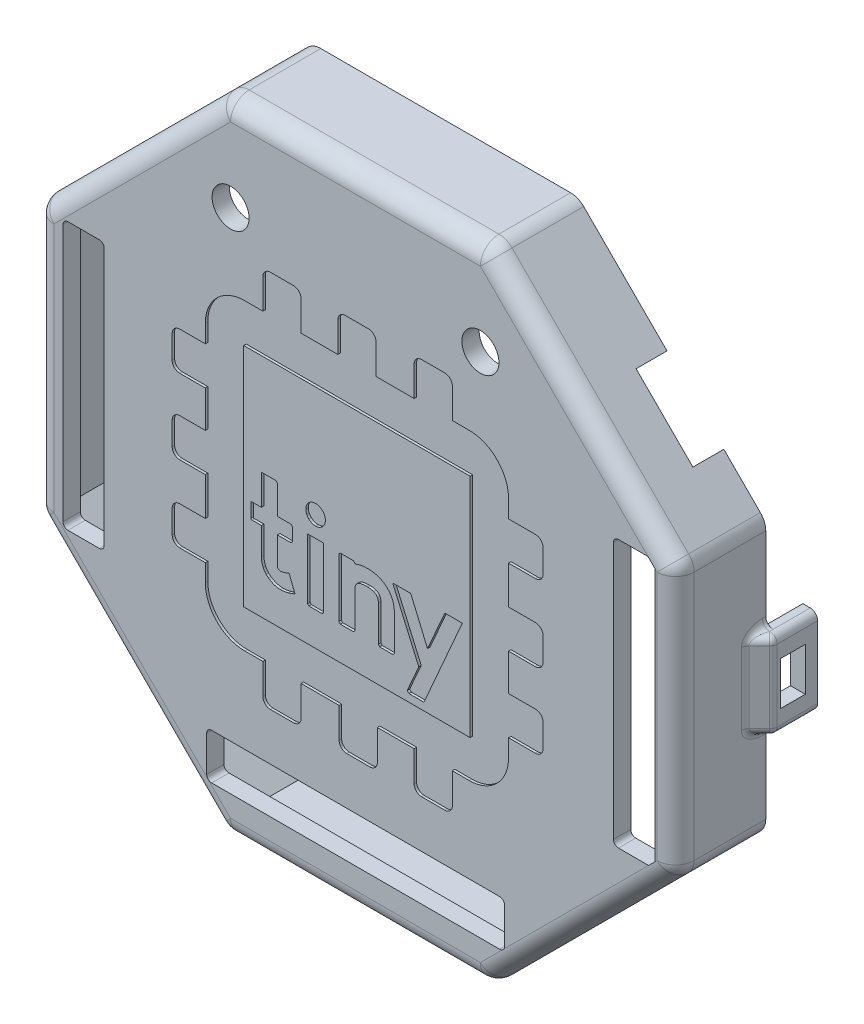
SolidWorks part; units mm, degrees
ref_plane "Front Plane" through (0, 0, 0) normal (0, 0, 1) x (1, 0, 0)
ref_plane "Top Plane" through (0, 0, 0) normal (0, 1, 0) x (1, 0, 0)
ref_plane "Right Plane" through (0, 0, 0) normal (1, 0, 0) x (0, 0, -1)
sketch "Sketch1" plane through (0, 0, 0) normal (0, 0, 1) x (1, 0, 0)
  line L0 (25.9, -10.1068) -> (25.9, 10.1068) construction
  line L1 (25.4607, 11.1675) -> (22.5059, 14.1222) construction
  line L2 (22.5059, 14.1222) -> (21.5159, 13.1323) construction
  line L3 (21.5159, 13.1323) -> (24.5, 10.1482) construction
  line L4 (24.5, 10.1482) -> (24.5, -10.1482) construction
  line L5 (24.5, -10.1482) -> (21.6927, -12.9555) construction
  line L6 (21.6927, -12.9555) -> (22.6827, -13.9455) construction
  line L7 (22.6827, -13.9455) -> (25.4607, -11.1675) construction
  line L8 (-16.1773, -20.4508) -> (-11.1675, -25.4607) construction
  line L9 (-10.1068, -25.9) -> (10.1068, -25.9) construction
  line L10 (11.1675, -25.4607) -> (15.6116, -21.0165) construction
  line L11 (15.6116, -21.0165) -> (14.6216, -20.0266) construction
  line L12 (14.6216, -20.0266) -> (10.1482, -24.5) construction
  line L13 (10.1482, -24.5) -> (-10.1482, -24.5) construction
  line L14 (-10.1482, -24.5) -> (-15.1873, -19.4609) construction
  line L15 (-15.1873, -19.4609) -> (-16.1773, -20.4508) construction
  line L16 (-22.117, 14.5112) -> (-25.4607, 11.1675) construction
  line L17 (-25.9, 10.1068) -> (-25.9, -10.1068) construction
  line L18 (-25.4607, -11.1675) -> (-22.1877, -14.4404) construction
  line L19 (-22.1877, -14.4404) -> (-21.1977, -13.4505) construction
  line L20 (-21.1977, -13.4505) -> (-24.5, -10.1482) construction
  line L21 (-24.5, -10.1482) -> (-24.5, 10.1482) construction
  line L22 (-24.5, 10.1482) -> (-21.127, 13.5212) construction
  line L23 (-21.127, 13.5212) -> (-22.117, 14.5112) construction
  line L24 (10.1068, 25.9) -> (-10.1068, 25.9) construction
  line L25 (-11.1675, 25.4607) -> (-17.5208, 19.1073) construction
  line L26 (-17.5208, 19.1073) -> (-16.5308, 18.1174) construction
  line L27 (-16.5308, 18.1174) -> (-10.1482, 24.5) construction
  line L28 (-10.1482, 24.5) -> (10.1482, 24.5) construction
  line L29 (10.1482, 24.5) -> (16.9197, 17.7285) construction
  line L30 (16.9197, 17.7285) -> (17.9097, 18.7184) construction
  line L31 (17.9097, 18.7184) -> (11.1675, 25.4607) construction
  line L32 (25.9, -10.1068) -> (25.9, 10.1068)
  line L33 (25.4607, 11.1675) -> (22.5059, 14.1222)
  line L34 (22.5059, 14.1222) -> (21.5159, 13.1323)
  line L35 (21.5159, 13.1323) -> (24.5, 10.1482)
  line L36 (24.5, 10.1482) -> (24.5, -10.1482)
  line L37 (24.5, -10.1482) -> (21.6927, -12.9555)
  line L38 (21.6927, -12.9555) -> (22.6827, -13.9455)
  line L39 (22.6827, -13.9455) -> (25.4607, -11.1675)
  line L40 (-16.1773, -20.4508) -> (-11.1675, -25.4607)
  line L41 (-10.1068, -25.9) -> (10.1068, -25.9)
  line L42 (11.1675, -25.4607) -> (15.6116, -21.0165)
  line L43 (15.6116, -21.0165) -> (14.6216, -20.0266)
  line L44 (14.6216, -20.0266) -> (10.1482, -24.5)
  line L45 (10.1482, -24.5) -> (-10.1482, -24.5)
  line L46 (-10.1482, -24.5) -> (-15.1873, -19.4609)
  line L47 (-15.1873, -19.4609) -> (-16.1773, -20.4508)
  line L48 (-22.117, 14.5112) -> (-25.4607, 11.1675)
  line L49 (-25.9, 10.1068) -> (-25.9, -10.1068)
  line L50 (-25.4607, -11.1675) -> (-22.1877, -14.4404)
  line L51 (-22.1877, -14.4404) -> (-21.1977, -13.4505)
  line L52 (-21.1977, -13.4505) -> (-24.5, -10.1482)
  line L53 (-24.5, -10.1482) -> (-24.5, 10.1482)
  line L54 (-24.5, 10.1482) -> (-21.127, 13.5212)
  line L55 (-21.127, 13.5212) -> (-22.117, 14.5112)
  line L56 (10.1068, 25.9) -> (-10.1068, 25.9)
  line L57 (-11.1675, 25.4607) -> (-17.5208, 19.1073)
  line L58 (-17.5208, 19.1073) -> (-16.5308, 18.1174)
  line L59 (-16.5308, 18.1174) -> (-10.1482, 24.5)
  line L60 (-10.1482, 24.5) -> (10.1482, 24.5)
  line L61 (10.1482, 24.5) -> (16.9197, 17.7285)
  line L62 (16.9197, 17.7285) -> (17.9097, 18.7184)
  line L63 (17.9097, 18.7184) -> (11.1675, 25.4607)
  line L66 (-17.5208, 19.1073) -> (-16.5308, 18.1174)
  line L67 (-21.127, 13.5212) -> (-22.117, 14.5112)
  arc A0 (25.9, 10.1068) -> (25.4607, 11.1675) centre (24.4, 10.1068) ccw construction
  arc A1 (25.4607, -11.1675) -> (25.9, -10.1068) centre (24.4, -10.1068) ccw construction
  arc A2 (-11.1675, -25.4607) -> (-10.1068, -25.9) centre (-10.1068, -24.4) ccw construction
  arc A3 (10.1068, -25.9) -> (11.1675, -25.4607) centre (10.1068, -24.4) ccw construction
  arc A4 (-25.4607, 11.1675) -> (-25.9, 10.1068) centre (-24.4, 10.1068) ccw construction
  arc A5 (-25.9, -10.1068) -> (-25.4607, -11.1675) centre (-24.4, -10.1068) ccw construction
  arc A6 (-10.1068, 25.9) -> (-11.1675, 25.4607) centre (-10.1068, 24.4) ccw construction
  arc A7 (11.1675, 25.4607) -> (10.1068, 25.9) centre (10.1068, 24.4) ccw construction
  arc A8 (25.9, 10.1068) -> (25.4607, 11.1675) centre (24.4, 10.1068) ccw
  arc A9 (25.4607, -11.1675) -> (25.9, -10.1068) centre (24.4, -10.1068) ccw
  arc A10 (-11.1675, -25.4607) -> (-10.1068, -25.9) centre (-10.1068, -24.4) ccw
  arc A11 (10.1068, -25.9) -> (11.1675, -25.4607) centre (10.1068, -24.4) ccw
  arc A12 (-25.4607, 11.1675) -> (-25.9, 10.1068) centre (-24.4, 10.1068) ccw
  arc A13 (-25.9, -10.1068) -> (-25.4607, -11.1675) centre (-24.4, -10.1068) ccw
  arc A14 (-10.1068, 25.9) -> (-11.1675, 25.4607) centre (-10.1068, 24.4) ccw
  arc A15 (11.1675, 25.4607) -> (10.1068, 25.9) centre (10.1068, 24.4) ccw
extrude "Boss-Extrude1" add sketch "Sketch1" along normal blind 5 contours L63 A15 L56 A14 L57 L58 L59 L60 L61 L62 | L49 A13 L50 L51 L52 L53 L54 L55 L48 A12 | L41 A11 L42 L43 L44 L45 L46 L47 L40 A10 | L39 A9 L32 A8 L33 L34 L35 L36 L37 L38 region at (24.747, 0.1144, 0) region at (-15.453, -20.1852, 0) region at (-24.631, 0.0454, 0) region at (10.5417, 25.4499, 0)
sketch "Sketch2" plane through (0, 0, 5) normal (0, 0, 1) x (1, 0, 0)
  line L0 (22.6827, -13.9455) -> (25.4607, -11.1675) construction
  line L1 (25.9, -10.1068) -> (25.9, 10.1068) construction
  line L2 (25.4607, 11.1675) -> (22.5059, 14.1222) construction
  line L3 (22.5059, 14.1222) -> (21.5159, 13.1323) construction
  line L4 (21.5159, 13.1323) -> (24.5, 10.1482) construction
  line L5 (24.5, 10.1482) -> (24.5, -10.1482) construction
  line L6 (24.5, -10.1482) -> (21.6927, -12.9555) construction
  line L7 (21.6927, -12.9555) -> (22.6827, -13.9455) construction
  line L8 (-10.1068, -25.9) -> (10.1068, -25.9) construction
  line L9 (11.1675, -25.4607) -> (15.6116, -21.0165) construction
  line L10 (15.6116, -21.0165) -> (14.6216, -20.0266) construction
  line L11 (14.6216, -20.0266) -> (10.1482, -24.5) construction
  line L12 (10.1482, -24.5) -> (-10.1482, -24.5) construction
  line L13 (-10.1482, -24.5) -> (-15.1873, -19.4609) construction
  line L14 (-15.1873, -19.4609) -> (-16.1773, -20.4508) construction
  line L15 (-16.1773, -20.4508) -> (-11.1675, -25.4607) construction
  line L16 (-25.9, 10.1068) -> (-25.9, -10.1068) construction
  line L17 (-25.4607, -11.1675) -> (-22.1877, -14.4404) construction
  line L18 (-22.1877, -14.4404) -> (-21.1977, -13.4505) construction
  line L19 (-21.1977, -13.4505) -> (-24.5, -10.1482) construction
  line L20 (-24.5, -10.1482) -> (-24.5, 10.1482) construction
  line L21 (-24.5, 10.1482) -> (-21.127, 13.5212) construction
  line L22 (-21.127, 13.5212) -> (-22.117, 14.5112) construction
  line L23 (-22.117, 14.5112) -> (-25.4607, 11.1675) construction
  line L24 (17.9097, 18.7184) -> (11.1675, 25.4607) construction
  line L25 (10.1068, 25.9) -> (-10.1068, 25.9) construction
  line L26 (-11.1675, 25.4607) -> (-17.5208, 19.1073) construction
  line L27 (-17.5208, 19.1073) -> (-16.5308, 18.1174) construction
  line L28 (-16.5308, 18.1174) -> (-10.1482, 24.5) construction
  line L29 (-10.1482, 24.5) -> (10.1482, 24.5) construction
  line L30 (10.1482, 24.5) -> (16.9197, 17.7285) construction
  line L31 (16.9197, 17.7285) -> (17.9097, 18.7184) construction
  line L32 (22.6827, -13.9455) -> (25.4607, -11.1675)
  line L33 (25.9, -10.1068) -> (25.9, 10.1068)
  line L34 (25.4607, 11.1675) -> (22.5059, 14.1222)
  line L35 (22.5059, 14.1222) -> (21.5159, 13.1323)
  line L36 (21.5159, 13.1323) -> (24.5, 10.1482)
  line L37 (24.5, 10.1482) -> (24.5, -10.1482)
  line L38 (24.5, -10.1482) -> (21.6927, -12.9555)
  line L39 (21.6927, -12.9555) -> (22.6827, -13.9455)
  line L40 (-10.1068, -25.9) -> (10.1068, -25.9)
  line L41 (11.1675, -25.4607) -> (15.6116, -21.0165)
  line L42 (15.6116, -21.0165) -> (14.6216, -20.0266)
  line L43 (14.6216, -20.0266) -> (10.1482, -24.5)
  line L44 (10.1482, -24.5) -> (-10.1482, -24.5)
  line L45 (-10.1482, -24.5) -> (-15.1873, -19.4609)
  line L46 (-15.1873, -19.4609) -> (-16.1773, -20.4508)
  line L47 (-16.1773, -20.4508) -> (-11.1675, -25.4607)
  line L48 (-25.9, 10.1068) -> (-25.9, -10.1068)
  line L49 (-25.4607, -11.1675) -> (-22.1877, -14.4404)
  line L50 (-22.1877, -14.4404) -> (-21.1977, -13.4505)
  line L51 (-21.1977, -13.4505) -> (-24.5, -10.1482)
  line L52 (-24.5, -10.1482) -> (-24.5, 10.1482)
  line L53 (-24.5, 10.1482) -> (-21.127, 13.5212)
  line L54 (-21.127, 13.5212) -> (-22.117, 14.5112)
  line L55 (-22.117, 14.5112) -> (-25.4607, 11.1675)
  line L56 (17.9097, 18.7184) -> (11.1675, 25.4607)
  line L57 (10.1068, 25.9) -> (-10.1068, 25.9)
  line L58 (-11.1675, 25.4607) -> (-17.5208, 19.1073)
  line L59 (-17.5208, 19.1073) -> (-16.5308, 18.1174)
  line L60 (-16.5308, 18.1174) -> (-10.1482, 24.5)
  line L61 (-10.1482, 24.5) -> (10.1482, 24.5)
  line L62 (10.1482, 24.5) -> (16.9197, 17.7285)
  line L63 (16.9197, 17.7285) -> (17.9097, 18.7184)
  line L64 (-22.117, 14.5112) -> (-17.5208, 19.1073)
  line L65 (-16.5308, 18.1174) -> (-21.127, 13.5212)
  line L66 (-21.1977, -13.4505) -> (-15.1873, -19.4609)
  line L67 (-16.1773, -20.4508) -> (-22.1877, -14.4404)
  line L68 (14.6216, -20.0266) -> (21.6927, -12.9555)
  line L69 (22.6827, -13.9455) -> (15.6116, -21.0165)
  line L70 (22.5059, 14.1222) -> (17.9097, 18.7184)
  line L71 (21.5159, 13.1323) -> (16.9197, 17.7285)
  arc A0 (25.4607, -11.1675) -> (25.9, -10.1068) centre (24.4, -10.1068) ccw construction
  arc A1 (25.9, 10.1068) -> (25.4607, 11.1675) centre (24.4, 10.1068) ccw construction
  arc A2 (10.1068, -25.9) -> (11.1675, -25.4607) centre (10.1068, -24.4) ccw construction
  arc A3 (-11.1675, -25.4607) -> (-10.1068, -25.9) centre (-10.1068, -24.4) ccw construction
  arc A4 (-25.9, -10.1068) -> (-25.4607, -11.1675) centre (-24.4, -10.1068) ccw construction
  arc A5 (-25.4607, 11.1675) -> (-25.9, 10.1068) centre (-24.4, 10.1068) ccw construction
  arc A6 (11.1675, 25.4607) -> (10.1068, 25.9) centre (10.1068, 24.4) ccw construction
  arc A7 (-10.1068, 25.9) -> (-11.1675, 25.4607) centre (-10.1068, 24.4) ccw construction
  arc A8 (25.4607, -11.1675) -> (25.9, -10.1068) centre (24.4, -10.1068) ccw
  arc A9 (25.9, 10.1068) -> (25.4607, 11.1675) centre (24.4, 10.1068) ccw
  arc A10 (10.1068, -25.9) -> (11.1675, -25.4607) centre (10.1068, -24.4) ccw
  arc A11 (-11.1675, -25.4607) -> (-10.1068, -25.9) centre (-10.1068, -24.4) ccw
  arc A12 (-25.9, -10.1068) -> (-25.4607, -11.1675) centre (-24.4, -10.1068) ccw
  arc A13 (-25.4607, 11.1675) -> (-25.9, 10.1068) centre (-24.4, 10.1068) ccw
  arc A14 (11.1675, 25.4607) -> (10.1068, 25.9) centre (10.1068, 24.4) ccw
  arc A15 (-10.1068, 25.9) -> (-11.1675, 25.4607) centre (-10.1068, 24.4) ccw
  line M21 (17.9097, 18.7184) -> (11.1675, 25.4607)
  arc M22 (11.1675, 25.4607) -> (10.1068, 25.9) centre (10.1068, 24.4) ccw
  line M23 (10.1068, 25.9) -> (-10.1068, 25.9)
  arc M24 (-10.1068, 25.9) -> (-11.1675, 25.4607) centre (-10.1068, 24.4) ccw
  line M25 (-11.1675, 25.4607) -> (-17.5208, 19.1073)
  line M26 (-17.5208, 19.1073) -> (-16.5308, 18.1174)
  line M27 (-16.5308, 18.1174) -> (-10.1482, 24.5)
  line M28 (-10.1482, 24.5) -> (10.1482, 24.5)
  line M29 (10.1482, 24.5) -> (16.9197, 17.7285)
  line M30 (16.9197, 17.7285) -> (17.9097, 18.7184)
extrude "Boss-Extrude2" add sketch "Sketch2" along normal blind 1.4 contours L36 L71 L65 L53 L52 L51 L66 L45 L44 L43 L68 L38 L37 M29 M28 M27 | L33 A9 L34 L35 L36 L37 L38 L39 L32 A8 | L69 L39 L68 L42 | L47 A11 L40 A10 L41 L42 L43 L44 L45 L46 | L67 L46 L66 L50 | L55 A13 L48 A12 L49 L50 L51 L52 L53 L54 | L65 L64 L54 M26 | M30 M21 M22 M23 M24 M25 M26 M27 M28 M29 | L71 L35 L70 M30 region at (24.747, 0.1144, 5) region at (18.6522, -16.986, 5) region at (0, 0, 5) region at (13.1602, -23.0093, 5) region at (19.7128, 15.9254, 5) region at (13.7911, 21.3714, 5) region at (-18.6875, -16.9507, 5) region at (-24.631, 0.0454, 5) region at (-19.3239, 16.3143, 5)
sketch "Sketch3" plane through (0, 0, 5) normal (0, 0, -1) x (-1, 0, 0)
  line L0 (-21.5159, 13.1323) -> (-16.9197, 17.7285)
  line L1 (-16.9197, 17.7285) -> (-17.9097, 18.7184)
  line L2 (-17.9097, 18.7184) -> (-22.5059, 14.1222)
  line L3 (-22.5059, 14.1222) -> (-21.5159, 13.1323)
  line L4 (21.127, 13.5212) -> (16.5308, 18.1174)
  line L5 (16.5308, 18.1174) -> (17.5208, 19.1073)
  line L6 (17.5208, 19.1073) -> (22.117, 14.5112)
  line L7 (22.117, 14.5112) -> (21.127, 13.5212)
extrude "Boss-Extrude3" add sketch "Sketch3" along normal blind 3.4 contours L7 L4 L5 L6 | L3 L0 L1 L2
sketch "Sketch4" plane through (0, 0, 5) normal (0, 0, -1) x (-1, 0, 0)
  line L0 (-15.6116, -21.0165) -> (-14.6216, -20.0266)
  line L1 (-14.6216, -20.0266) -> (-21.6927, -12.9555)
  line L2 (-21.6927, -12.9555) -> (-22.6827, -13.9455)
  line L3 (-22.6827, -13.9455) -> (-15.6116, -21.0165)
extrude "Boss-Extrude4" add sketch "Sketch4" along normal blind 3.4
sketch "Sketch5" plane through (0, 0, 5) normal (0, 0, -1) x (-1, 0, 0)
  line L0 (16.1773, -20.4508) -> (22.1877, -14.4404)
  line L1 (22.1877, -14.4404) -> (21.1977, -13.4505)
  line L2 (21.1977, -13.4505) -> (15.1873, -19.4609)
  line L3 (15.1873, -19.4609) -> (16.1773, -20.4508)
extrude "Boss-Extrude5" add sketch "Sketch5" along normal blind 1
fillet "Fillet1" radius 1.5 18 edges at (10.6808, -25.7858, 6.4) (0, -25.9, 6.4) (-10.6808, -25.7858, 6.4) (-18.3141, -18.3141, 6.4) (-25.7858, -10.6808, 6.4) (-25.9, 0, 6.4) (-25.7858, 10.6808, 6.4) (-18.3141, 18.3141, 6.4) (-10.6808, 25.7858, 6.4) (0, 25.9, 6.4) (10.6808, 25.7858, 6.4) (18.3141, 18.3141, 6.4) (25.7858, 10.6808, 6.4) (25.9, 0, 6.4) (25.7858, -10.6808, 6.4) (18.3141, -18.3141, 6.4) (15.1166, -20.5216, 1.6) (22.1877, -13.4505, 1.6)
sketch "Sketch6" plane through (0, 0, 6.4) normal (0, 0, 1) x (1, 0, 0)
  line L0 (-23.2729, -10.394) -> (-20.7329, -10.394) construction
  line L1 (-23.2729, 10.434) -> (-23.2729, -10.394) construction
  line L2 (-20.7329, -10.394) -> (-20.7329, 10.434) construction
  line L3 (-20.7329, 10.434) -> (-23.2729, 10.434) construction
  line L4 (21.2779, -10.389) -> (23.8179, -10.389) construction
  line L5 (23.8179, -10.389) -> (23.8179, 10.439) construction
  line L6 (21.2779, 10.439) -> (21.2779, -10.389) construction
  line L7 (23.8179, 10.439) -> (21.2779, 10.439) construction
  line L8 (-23.2729, -10.394) -> (-20.7329, -10.394)
  line L9 (-23.2729, 10.434) -> (-23.2729, -10.394)
  line L10 (-20.7329, -10.394) -> (-20.7329, 10.434)
  line L11 (-20.7329, 10.434) -> (-23.2729, 10.434)
  line L12 (21.2779, -10.389) -> (23.8179, -10.389)
  line L13 (23.8179, -10.389) -> (23.8179, 10.439)
  line L14 (21.2779, 10.439) -> (21.2779, -10.389)
  line L15 (23.8179, 10.439) -> (21.2779, 10.439)
  line L16 (-20.3329, -10.394) -> (-20.3329, 10.434)
  line L17 (-20.7329, 10.834) -> (-23.2729, 10.834)
  line L18 (-23.6729, 10.434) -> (-23.6729, -10.394)
  line L19 (-23.2729, -10.794) -> (-20.7329, -10.794)
  line L20 (21.2779, -10.789) -> (23.8179, -10.789)
  line L21 (24.2179, -10.389) -> (24.2179, 10.439)
  line L22 (23.8179, 10.839) -> (21.2779, 10.839)
  line L23 (20.8779, 10.439) -> (20.8779, -10.389)
  line L24 (24.2179, 10.839) -> (20.8779, 10.839) construction
  line L25 (20.8779, 10.839) -> (20.8779, -10.789) construction
  line L26 (24.2179, -10.789) -> (24.2179, 10.839) construction
  line L27 (20.8779, -10.789) -> (24.2179, -10.789) construction
  line L28 (-20.3329, -10.794) -> (-20.3329, 10.834) construction
  line L29 (-23.6729, -10.794) -> (-20.3329, -10.794) construction
  line L30 (-23.6729, 10.834) -> (-23.6729, -10.794) construction
  line L31 (-20.3329, 10.834) -> (-23.6729, 10.834) construction
  arc A0 (21.2779, 10.839) -> (20.8779, 10.439) centre (21.2779, 10.439) ccw
  arc A1 (24.2179, 10.439) -> (23.8179, 10.839) centre (23.8179, 10.439) ccw
  arc A2 (23.8179, -10.789) -> (24.2179, -10.389) centre (23.8179, -10.389) ccw
  arc A3 (21.2779, -10.789) -> (20.8779, -10.389) centre (21.2779, -10.389) cw
  arc A4 (-20.3329, -10.394) -> (-20.7329, -10.794) centre (-20.7329, -10.394) cw
  arc A5 (-23.6729, -10.394) -> (-23.2729, -10.794) centre (-23.2729, -10.394) ccw
  arc A6 (-20.3329, 10.434) -> (-20.7329, 10.834) centre (-20.7329, 10.434) ccw
  arc A7 (-23.2729, 10.834) -> (-23.6729, 10.434) centre (-23.2729, 10.434) ccw
  line M15 (10.1068, -24.4) -> (24.4, -10.1068)
  line M17 (24.4, 10.1068) -> (10.1068, 24.4)
  dimension "D2" = 0.4
  dimension "D1" = 0.4
extrude "Cut-Extrude1" cut sketch "Sketch6" against normal through all contours L10 L11 L9 L8 | L17 A7 L18 A5 L19 A4 L16 A6 L11 L10 L8 L9 | L13 L15 L14 L12 | A3 L20 L21 L22 A0 L23 L15 L13 L12 L14 M15 M17 region at (-22.0029, 0.02, 6.4) region at (22.5479, 0.025, 6.4) region at (-20.6048, -10.5221, 6.4) region at (21.1499, -10.5171, 6.4)
sketch "Sketch7" plane through (0, 0, 6.4) normal (0, 0, 1) x (1, 0, 0)
  line L0 (9.3915, -22.0846) -> (11.6775, -22.0846) construction
  line L1 (11.6775, -22.0846) -> (11.6775, -19.5954) construction
  line L2 (-11.1825, -22.0846) -> (-8.8965, -22.0846) construction
  line L3 (-11.1825, -19.5954) -> (-11.1825, -22.0846) construction
  line L4 (9.3915, -22.0846) -> (11.6775, -22.0846)
  line L5 (11.6775, -22.0846) -> (11.6775, -19.5954)
  line L6 (-11.1825, -22.0846) -> (-8.8965, -22.0846)
  line L7 (-11.1825, -19.5954) -> (-11.1825, -22.0846)
  line L8 (-11.1825, -19.5954) -> (11.6775, -19.5954)
  line L9 (9.3915, -22.0846) -> (-8.8965, -22.0846)
  line L10 (9.3915, -22.6846) -> (-8.8965, -22.6846)
  line L11 (-11.6409, -22.6846) -> (-8.8965, -22.6846)
  line L12 (-12.0409, -19.3954) -> (-12.0409, -22.2846)
  line L13 (-11.6409, -18.9954) -> (11.6667, -18.9954)
  line L14 (12.0667, -22.2846) -> (12.0667, -19.3954)
  line L15 (9.3915, -22.6846) -> (11.6667, -22.6846)
  arc A0 (11.6667, -18.9954) -> (12.0667, -19.3954) centre (11.6667, -19.3954) cw
  arc A1 (12.0667, -22.2846) -> (11.6667, -22.6846) centre (11.6667, -22.2846) cw
  arc A2 (-11.6409, -22.6846) -> (-12.0409, -22.2846) centre (-11.6409, -22.2846) cw
  arc A3 (-12.0409, -19.3954) -> (-11.6409, -18.9954) centre (-11.6409, -19.3954) cw
  dimension "D2" = 0.4
  dimension "D1" = 0.6
  dimension "D3" = 0.6
extrude "Cut-Extrude2" cut sketch "Sketch7" against normal through all contours L9 L4 L5 L8 L7 L6 | A3 L12 A2 L11 L10 L15 A1 L14 A0 L13 L4 L9 L6 L7 L8 L5 | L9 L6 L7 L8 L5 L4 | L10 L11 A2 L12 A3 L13 A0 L14 A1 L15 region at (0.2475, -20.84, 6.4) region at (0.2475, -22.4407, 6.4)
sketch "Sketch10" plane through (0, 0, 6.4) normal (0, 0, 1) x (1, 0, 0)
  line L0 (6.3526, -0.709) -> (-6.1073, -0.709)
  line L1 (-6.1073, -0.709) -> (-6.1073, 11.751)
  line L2 (-6.1073, 11.751) -> (6.3526, 11.751)
  line L3 (6.3526, 11.751) -> (6.3526, -0.709)
  line L4 (10.3637, 9.084) -> (10.3637, 10.3555)
  line L5 (9.9467, 10.7717) -> (8.4679, 10.7717)
  line L6 (8.4679, 10.7717) -> (8.4679, 11.7461)
  line L7 (6.3004, 13.9128) -> (5.3733, 13.9128)
  line L8 (5.3733, 13.9128) -> (5.3733, 15.5588)
  line L9 (4.9563, 15.9758) -> (3.6857, 15.9758)
  line L10 (3.2686, 15.5588) -> (3.2686, 13.9128)
  line L11 (3.2686, 13.9128) -> (1.1746, 13.9128)
  line L12 (1.1746, 13.9128) -> (1.1746, 15.5588)
  line L13 (0.7584, 15.9758) -> (-0.5131, 15.9758)
  line L14 (-0.9293, 15.5588) -> (-0.9293, 13.9128)
  line L15 (-0.9293, 13.9128) -> (-2.9507, 13.9128)
  line L16 (-2.9507, 13.9128) -> (-2.9507, 15.5588)
  line L17 (-3.3678, 15.9758) -> (-4.6384, 15.9758)
  line L18 (-5.0554, 15.5588) -> (-5.0554, 13.9128)
  line L19 (-5.0554, 13.9128) -> (-6.0551, 13.9128)
  line L20 (-8.2226, 11.7461) -> (-8.2226, 10.7717)
  line L21 (-8.2226, 10.7717) -> (-9.6287, 10.7717)
  line L22 (-10.0458, 10.3555) -> (-10.0458, 9.084)
  line L23 (-9.6287, 8.6678) -> (-8.2226, 8.6678)
  line L24 (-8.2226, 8.6678) -> (-8.2226, 6.6463)
  line L25 (-8.2226, 6.6463) -> (-9.6287, 6.6463)
  line L26 (-10.0458, 6.2293) -> (-10.0458, 4.9587)
  line L27 (-9.6287, 4.5417) -> (-8.2226, 4.5417)
  line L28 (-8.2226, 4.5417) -> (-8.2226, 2.4476)
  line L29 (-8.2226, 2.4476) -> (-9.6287, 2.4476)
  line L30 (-10.0458, 2.0314) -> (-10.0458, 0.7599)
  line L31 (-9.6287, 0.3437) -> (-8.2226, 0.3437)
  line L32 (-8.2226, 0.3437) -> (-8.2226, -0.6095)
  line L33 (-6.0551, -2.777) -> (-5.0554, -2.777)
  line L34 (-5.0554, -2.777) -> (-5.0554, -4.4434)
  line L35 (-4.6384, -4.8604) -> (-3.3678, -4.8604)
  line L36 (-2.9507, -4.4434) -> (-2.9507, -2.777)
  line L37 (-2.9507, -2.777) -> (-0.8567, -2.777)
  line L38 (-0.8567, -2.777) -> (-0.8567, -4.4434)
  line L39 (-0.4396, -4.8604) -> (0.831, -4.8604)
  line L40 (1.248, -4.4434) -> (1.248, -2.777)
  line L41 (1.248, -2.777) -> (3.2686, -2.777)
  line L42 (3.2686, -2.777) -> (3.2686, -4.4434)
  line L43 (3.6857, -4.8604) -> (4.9563, -4.8604)
  line L44 (5.3733, -4.4434) -> (5.3733, -2.777)
  line L45 (5.3733, -2.777) -> (6.3004, -2.777)
  line L46 (8.4679, -0.6095) -> (8.4679, 0.3437)
  line L47 (8.4679, 0.3437) -> (9.9467, 0.3437)
  line L48 (10.3637, 0.7599) -> (10.3637, 2.0314)
  line L49 (9.9467, 2.4476) -> (8.4679, 2.4476)
  line L50 (8.4679, 2.4476) -> (8.4679, 4.469)
  line L51 (8.4679, 4.469) -> (9.9467, 4.469)
  line L52 (10.3637, 4.8861) -> (10.3637, 6.1567)
  line L53 (9.9467, 6.5737) -> (8.4679, 6.5737)
  line L54 (8.4679, 6.5737) -> (8.4679, 8.6678)
  line L55 (8.4679, 8.6678) -> (9.9467, 8.6678)
  line L56 (-2.4121, 7.0577) -> (-2.4121, 1.1786)
  line L57 (-2.5949, 0.9966) -> (-4.0639, 0.9966)
  line L58 (-4.2459, 1.1786) -> (-4.2459, 7.0577)
  line L59 (-4.2459, 7.0577) -> (-2.4121, 7.0577)
  line L60 (-14.5424, -8.9455) -> (-13.4977, -8.9455)
  line L61 (-13.4977, -8.9455) -> (-13.4977, -12.8799)
  line L62 (-13.4977, -12.8799) -> (-13.5822, -12.9643)
  line L63 (-13.5822, -12.9643) -> (-13.6459, -12.9681)
  line L64 (-13.6459, -12.9681) -> (-14.455, -12.9681)
  line L65 (-14.455, -12.9681) -> (-14.5385, -12.8827)
  line L66 (-14.5385, -12.8827) -> (-14.5424, -12.8198)
  line L67 (-14.5424, -12.8198) -> (-14.5424, -8.9455)
  line L68 (-13.3848, -7.597) -> (-13.3848, -7.6205)
  line L69 (-13.5529, -8.0427) -> (-13.561, -8.0512)
  line L70 (-14.0085, -8.2442) -> (-14.0319, -8.2442)
  line L71 (-14.4569, -8.0698) -> (-14.4636, -8.0631)
  line L72 (-14.6556, -7.6244) -> (-14.6556, -7.5931)
  line L73 (-14.4729, -7.16) -> (-14.4615, -7.1491)
  line L74 (-14.4615, -7.1491) -> (-14.3878, -7.0868)
  line L75 (-14.0358, -6.9733) -> (-14.0045, -6.9733)
  line L76 (-13.5861, -7.1413) -> (-13.5777, -7.1494)
  line L77 (-10.1353, -10.1363) -> (-10.155, -10.1279)
  line L78 (-10.155, -10.1279) -> (-10.1658, -10.1173)
  line L79 (-11.5056, -10.3384) -> (-11.5158, -10.355)
  line L80 (-11.3171, -11.8101) -> (-11.308, -11.8164)
  line L81 (-9.731, -10.9843) -> (-9.731, -10.9723)
  line L82 (-10.7052, -13.0616) -> (-10.7404, -13.0616)
  line L83 (-11.8353, -12.727) -> (-11.8441, -12.721)
  line L84 (-12.7555, -11.0036) -> (-12.7555, -10.9452)
  line L85 (-12.1524, -9.4873) -> (-12.1438, -9.4789)
  line L86 (-9.2496, -9.5351) -> (-9.2455, -9.5393)
  line L87 (-5.8737, -12.7382) -> (-6.0038, -12.793)
  line L88 (-6.8004, -12.9678) -> (-6.8082, -12.9678)
  line L89 (-7.7454, -12.5779) -> (-7.7604, -12.5614)
  line L90 (-7.7604, -12.5614) -> (-7.8266, -12.4749)
  line L91 (-8.0594, -11.7521) -> (-8.0594, -6.9733)
  line L92 (-8.0594, -6.9733) -> (-7.1072, -6.9733)
  line L93 (-7.1072, -6.9733) -> (-7.0226, -7.0577)
  line L94 (-7.0226, -7.0577) -> (-7.0187, -7.1213)
  line L95 (-7.0187, -7.1213) -> (-7.0187, -8.942)
  line L96 (-7.0187, -8.942) -> (-6.1361, -8.942)
  line L97 (-6.1361, -8.942) -> (-6.0512, -9.0261)
  line L98 (-6.0512, -9.0261) -> (-6.0474, -9.09)
  line L99 (-6.0474, -9.09) -> (-6.0474, -9.8979)
  line L100 (-6.0474, -9.8979) -> (-6.1319, -9.9827)
  line L101 (-6.1319, -9.9827) -> (-6.1954, -9.9865)
  line L102 (-6.1954, -9.9865) -> (-7.0187, -9.9865)
  line L103 (-7.0187, -9.9865) -> (-7.0187, -11.7243)
  line L104 (-6.4276, -11.8375) -> (-6.2631, -11.7573)
  line L105 (-6.2631, -11.7573) -> (-5.8737, -12.7382)
  line L106 (-3.3843, -9.9317) -> (-3.4467, -9.9317)
  line L107 (-3.4544, -12.0171) -> (-3.3686, -12.0171)
  line L108 (-1.377, -9.038) -> (-1.377, -12.876)
  line L109 (-1.377, -12.876) -> (-1.4692, -12.9681)
  line L110 (-1.4692, -12.9681) -> (-2.309, -12.9681)
  line L111 (-2.309, -12.9681) -> (-2.4215, -12.8936)
  line L112 (-2.4215, -12.8936) -> (-2.4215, -12.7611)
  line L113 (-3.3998, -13.0616) -> (-3.4036, -13.0616)
  line L114 (-2.4215, -9.2039) -> (-2.4215, -9.0201)
  line L115 (-2.4215, -9.0201) -> (-2.309, -8.9455)
  line L116 (-2.309, -8.9455) -> (-1.4692, -8.9455)
  line L117 (-1.4692, -8.9455) -> (-1.377, -9.038)
  line L118 (4.3331, -11.5371) -> (4.3331, -11.5529)
  line L119 (-0.7141, -10.1572) -> (-0.7141, -10.134)
  line L120 (1.979, -7.2927) -> (1.9868, -7.2927)
  line L121 (1.9516, -12.2427) -> (2.0335, -12.2427)
  line L122 (3.6746, -11.1905) -> (4.3331, -11.5371)
  line L123 (7.7893, -11.1107) -> (7.7893, -11.0991)
  line L124 (6.671, -13.0439) -> (6.6358, -13.0439)
  line L125 (4.7648, -11.13) -> (4.7648, -11.0716)
  line L126 (11.6934, -9.4189) -> (11.6934, -9.4228)
  line L127 (10.8514, -9.953) -> (10.7892, -9.953)
  line L128 (9.9159, -11.2196) -> (9.9159, -12.9349)
  line L129 (9.9159, -12.9349) -> (9.9082, -12.9465)
  line L130 (9.9082, -12.9465) -> (9.179, -12.9465)
  line L131 (9.179, -12.9465) -> (9.1674, -12.9349)
  line L132 (9.1674, -12.9349) -> (9.1674, -9.2748)
  line L133 (9.1674, -9.2748) -> (9.179, -9.2671)
  line L134 (9.179, -9.2671) -> (9.9082, -9.2671)
  line L135 (9.9082, -9.2671) -> (9.9159, -9.2748)
  line L136 (9.9159, -9.2748) -> (9.9159, -9.5553)
  line L137 (10.7966, -9.1929) -> (10.8943, -9.1929)
  line L138 (12.8553, -10.4754) -> (12.7878, -10.6195)
  line L139 (12.7878, -10.6195) -> (14.8381, -10.6195)
  line L140 (14.8381, -10.6195) -> (14.8381, -10.6157)
  line L141 (15.7554, -11.1029) -> (15.7554, -11.22)
  line L142 (15.7385, -11.329) -> (12.7115, -11.329)
  line L143 (13.8193, -13.0439) -> (13.8021, -13.0439)
  line L144 (11.8745, -11.1107) -> (11.8745, -11.0952)
  line L145 (13.7515, -9.1577) -> (13.8741, -9.1577)
  spline S0 degree 3 poles (9.9467, 8.6678) (10.1768, 8.6678) (10.3637, 8.8539) (10.3637, 9.084) knots 0 0 0 0 1 1 1 1
  spline S1 degree 3 poles (10.3637, 10.3555) (10.3637, 10.5856) (10.1768, 10.7717) (9.9467, 10.7717) knots 2 2 2 2 3 3 3 3
  spline S2 degree 3 poles (8.4679, 11.7461) (8.4679, 12.9424) (7.4976, 13.9128) (6.3004, 13.9128) knots 5 5 5 5 6 6 6 6
  spline S3 degree 3 poles (5.3733, 15.5588) (5.3733, 15.7889) (5.1864, 15.9758) (4.9563, 15.9758) knots 8 8 8 8 9 9 9 9
  spline S4 degree 3 poles (3.6857, 15.9758) (3.4555, 15.9758) (3.2686, 15.7889) (3.2686, 15.5588) knots 10 10 10 10 11 11 11 11
  spline S5 degree 3 poles (1.1746, 15.5588) (1.1746, 15.7889) (0.9885, 15.9758) (0.7584, 15.9758) knots 14 14 14 14 15 15 15 15
  spline S6 degree 3 poles (-0.5131, 15.9758) (-0.7432, 15.9758) (-0.9293, 15.7889) (-0.9293, 15.5588) knots 16 16 16 16 17 17 17 17
  spline S7 degree 3 poles (-2.9507, 15.5588) (-2.9507, 15.7889) (-3.1376, 15.9758) (-3.3678, 15.9758) knots 20 20 20 20 21 21 21 21
  spline S8 degree 3 poles (-4.6384, 15.9758) (-4.8685, 15.9758) (-5.0554, 15.7889) (-5.0554, 15.5588) knots 22 22 22 22 23 23 23 23
  spline S9 degree 3 poles (-6.0551, 13.9128) (-7.2523, 13.9128) (-8.2226, 12.9424) (-8.2226, 11.7461) knots 25 25 25 25 26 26 26 26
  spline S10 degree 3 poles (-9.6287, 10.7717) (-9.8589, 10.7717) (-10.0458, 10.5856) (-10.0458, 10.3555) knots 28 28 28 28 29 29 29 29
  spline S11 degree 3 poles (-10.0458, 9.084) (-10.0458, 8.8539) (-9.8589, 8.6678) (-9.6287, 8.6678) knots 30 30 30 30 31 31 31 31
  spline S12 degree 3 poles (-9.6287, 6.6463) (-9.8589, 6.6463) (-10.0458, 6.4595) (-10.0458, 6.2293) knots 34 34 34 34 35 35 35 35
  spline S13 degree 3 poles (-10.0458, 4.9587) (-10.0458, 4.7286) (-9.8589, 4.5417) (-9.6287, 4.5417) knots 36 36 36 36 37 37 37 37
  spline S14 degree 3 poles (-9.6287, 2.4476) (-9.8589, 2.4476) (-10.0458, 2.2615) (-10.0458, 2.0314) knots 40 40 40 40 41 41 41 41
  spline S15 degree 3 poles (-10.0458, 0.7599) (-10.0458, 0.5298) (-9.8589, 0.3437) (-9.6287, 0.3437) knots 42 42 42 42 43 43 43 43
  spline S16 degree 3 poles (-8.2226, -0.6095) (-8.2226, -1.8067) (-7.2523, -2.777) (-6.0551, -2.777) knots 45 45 45 45 46 46 46 46
  spline S17 degree 3 poles (-5.0554, -4.4434) (-5.0554, -4.6736) (-4.8685, -4.8604) (-4.6384, -4.8604) knots 48 48 48 48 49 49 49 49
  spline S18 degree 3 poles (-3.3678, -4.8604) (-3.1376, -4.8604) (-2.9507, -4.6736) (-2.9507, -4.4434) knots 50 50 50 50 51 51 51 51
  spline S19 degree 3 poles (-0.8567, -4.4434) (-0.8567, -4.6736) (-0.6698, -4.8604) (-0.4396, -4.8604) knots 54 54 54 54 55 55 55 55
  spline S20 degree 3 poles (0.831, -4.8604) (1.0611, -4.8604) (1.248, -4.6736) (1.248, -4.4434) knots 56 56 56 56 57 57 57 57
  spline S21 degree 3 poles (3.2686, -4.4434) (3.2686, -4.6736) (3.4555, -4.8604) (3.6857, -4.8604) knots 60 60 60 60 61 61 61 61
  spline S22 degree 3 poles (4.9563, -4.8604) (5.1864, -4.8604) (5.3733, -4.6736) (5.3733, -4.4434) knots 62 62 62 62 63 63 63 63
  spline S23 degree 3 poles (6.3004, -2.777) (7.4976, -2.777) (8.4679, -1.8067) (8.4679, -0.6095) knots 65 65 65 65 66 66 66 66
  spline S24 degree 3 poles (9.9467, 0.3437) (10.1768, 0.3437) (10.3637, 0.5298) (10.3637, 0.7599) knots 68 68 68 68 69 69 69 69
  spline S25 degree 3 poles (10.3637, 2.0314) (10.3637, 2.2615) (10.1768, 2.4476) (9.9467, 2.4476) knots 70 70 70 70 71 71 71 71
  spline S26 degree 3 poles (9.9467, 4.469) (10.1768, 4.469) (10.3637, 4.6559) (10.3637, 4.8861) knots 74 74 74 74 75 75 75 75
  spline S27 degree 3 poles (10.3637, 6.1567) (10.3637, 6.3868) (10.1768, 6.5737) (9.9467, 6.5737) knots 76 76 76 76 77 77 77 77
  spline S28 degree 3 poles (-2.4121, 1.1786) (-2.4121, 1.0782) (-2.4937, 0.9966) (-2.5949, 0.9966) knots 1 1 1 1 2 2 2 2
  spline S29 degree 3 poles (-4.0639, 0.9966) (-4.1643, 0.9966) (-4.2459, 1.0782) (-4.2459, 1.1786) knots 3 3 3 3 4 4 4 4
  spline S30 degree 3 poles (-4.3813, 9.2195) (-4.3813, 9.8005) (-3.9104, 10.2722) (-2.7483, 10.2722) (-2.2766, 9.8005) (-2.2766, 9.2195) knots 2 2 2 2 3 3 4 4 4 4
  spline S31 degree 3 poles (-2.2766, 9.2195) (-2.2766, 8.6384) (-2.7483, 8.1675) (-3.9104, 8.1675) (-4.3813, 8.6384) (-4.3813, 9.2195) knots 0 0 0 0 1 1 2 2 2 2
  spline S32 degree 3 poles (-13.3848, -7.6205) (-13.3848, -7.7724) (-13.4413, -7.9144) (-13.5529, -8.0427) knots 1 1 1 1 2 2 2 2
  spline S33 degree 3 poles (-13.561, -8.0512) (-13.6923, -8.1791) (-13.8429, -8.2442) (-14.0085, -8.2442) knots 3 3 3 3 4 4 4 4
  spline S34 degree 3 poles (-14.0319, -8.2442) (-14.1883, -8.2442) (-14.3312, -8.1855) (-14.4569, -8.0698) knots 5 5 5 5 6 6 6 6
  spline S35 degree 3 poles (-14.4636, -8.0631) (-14.5315, -7.9918) (-14.5766, -7.9274) (-14.6019, -7.8662) knots 7 7 7 7 8 8 8 8
  spline S36 degree 3 poles (-14.6019, -7.8662) (-14.6369, -7.7868) (-14.6556, -7.7042) (-14.6556, -7.6244) knots 8 8 8 8 9 9 9 9
  spline S37 degree 3 poles (-14.6556, -7.5931) (-14.6556, -7.4366) (-14.594, -7.2911) (-14.4729, -7.16) knots 10 10 10 10 11 11 11 11
  spline S38 degree 3 poles (-14.3878, -7.0868) (-14.2734, -7.0116) (-14.1549, -6.9733) (-14.0358, -6.9733) knots 13 13 13 13 14 14 14 14
  spline S39 degree 3 poles (-14.0045, -6.9733) (-13.8549, -6.9733) (-13.7142, -7.0299) (-13.5861, -7.1413) knots 15 15 15 15 16 16 16 16
  spline S40 degree 3 poles (-13.5777, -7.1494) (-13.4497, -7.2809) (-13.3847, -7.4314) (-13.3848, -7.597) knots 17 17 17 17 18 18 18 18
  spline S41 degree 3 poles (-10.0042, -10.2597) (-10.0997, -10.1584) (-10.1318, -10.138) (-10.1353, -10.1363) knots 0 0 0 0 1 1 1 1
  spline S42 degree 3 poles (-10.1658, -10.1173) (-10.2021, -10.0871) (-10.2362, -10.0635) (-10.2668, -10.047) knots 3 3 3 3 4 4 4 4
  spline S43 degree 3 poles (-10.2668, -10.047) (-10.414, -9.9679) (-10.5681, -9.9278) (-10.7249, -9.9278) knots 4 4 4 4 5 5 5 5
  spline S44 degree 3 poles (-10.7249, -9.9278) (-10.9657, -9.9278) (-11.1816, -10.0164) (-11.3846, -10.1989) knots 5 5 5 5 6 6 6 6
  spline S45 degree 3 poles (-11.3846, -10.1989) (-11.4771, -10.2913) (-11.5006, -10.3293) (-11.5056, -10.3384) knots 6 6 6 6 7 7 7 7
  spline S46 degree 3 poles (-11.5158, -10.355) (-11.6497, -10.5416) (-11.7149, -10.7462) (-11.7149, -10.98) knots 8 8 8 8 9 9 9 9
  spline S47 degree 3 poles (-11.7149, -10.98) (-11.7149, -11.2321) (-11.6346, -11.455) (-11.4695, -11.6621) knots 9 9 9 9 10 10 10 10
  spline S48 degree 3 poles (-11.4695, -11.6621) (-11.3808, -11.7619) (-11.3356, -11.7981) (-11.3171, -11.8101) knots 10 10 10 10 11 11 11 11
  spline S49 degree 3 poles (-11.308, -11.8164) (-11.1269, -11.9539) (-10.9362, -12.0207) (-10.7249, -12.0207) knots 12 12 12 12 13 13 13 13
  spline S50 degree 3 poles (-10.7249, -12.0207) (-10.4655, -12.0207) (-10.2408, -11.9247) (-10.0385, -11.7268) knots 13 13 13 13 14 14 14 14
  spline S51 degree 3 poles (-10.0385, -11.7268) (-9.9611, -11.6448) (-9.9047, -11.5721) (-9.8745, -11.5141) knots 14 14 14 14 15 15 15 15
  spline S52 degree 3 poles (-9.8745, -11.5141) (-9.7787, -11.3407) (-9.731, -11.1636) (-9.731, -10.9843) knots 15 15 15 15 16 16 16 16
  spline S53 degree 3 poles (-9.731, -10.9723) (-9.731, -10.7069) (-9.8203, -10.4738) (-10.0042, -10.2597) knots 17 17 17 17 18 18 18 18
  spline S54 degree 3 poles (-8.6901, -10.98) (-8.6901, -11.3295) (-8.7757, -11.6695) (-8.9444, -11.9904) knots 0 0 0 0 1 1 1 1
  spline S55 degree 3 poles (-8.9444, -11.9904) (-9.0042, -12.0987) (-9.0835, -12.2144) (-9.1816, -12.3371) knots 1 1 1 1 2 2 2 2
  spline S56 degree 3 poles (-9.1816, -12.3371) (-9.2946, -12.4675) (-9.3821, -12.5547) (-9.4533, -12.6078) knots 2 2 2 2 3 3 3 3
  spline S57 degree 3 poles (-9.4533, -12.6078) (-9.5231, -12.6651) (-9.5948, -12.7171) (-9.6621, -12.7593) knots 3 3 3 3 4 4 4 4
  spline S58 degree 3 poles (-9.6621, -12.7593) (-9.9945, -12.9604) (-10.3449, -13.0616) (-10.7052, -13.0616) knots 4 4 4 4 5 5 5 5
  spline S59 degree 3 poles (-10.7404, -13.0616) (-11.1202, -13.0616) (-11.4887, -12.9491) (-11.8353, -12.727) knots 6 6 6 6 7 7 7 7
  spline S60 degree 3 poles (-11.8441, -12.721) (-11.909, -12.6725) (-11.967, -12.6264) (-12.0183, -12.5832) knots 8 8 8 8 9 9 9 9
  spline S61 degree 3 poles (-12.0183, -12.5832) (-12.1269, -12.4914) (-12.2048, -12.4134) (-12.256, -12.3455) knots 9 9 9 9 10 10 10 10
  spline S62 degree 3 poles (-12.256, -12.3455) (-12.3136, -12.2791) (-12.3678, -12.2066) (-12.417, -12.13) knots 10 10 10 10 11 11 11 11
  spline S63 degree 3 poles (-12.417, -12.13) (-12.4727, -12.0411) (-12.5202, -11.9542) (-12.5588, -11.8712) knots 11 11 11 11 12 12 12 12
  spline S64 degree 3 poles (-12.5588, -11.8712) (-12.6896, -11.5823) (-12.7555, -11.2908) (-12.7555, -11.0036) knots 12 12 12 12 13 13 13 13
  spline S65 degree 3 poles (-12.7555, -10.9452) (-12.7555, -10.633) (-12.6771, -10.3163) (-12.5223, -10.0041) knots 14 14 14 14 15 15 15 15
  spline S66 degree 3 poles (-12.5223, -10.0041) (-12.4775, -9.9169) (-12.4244, -9.829) (-12.3639, -9.7408) knots 15 15 15 15 16 16 16 16
  spline S67 degree 3 poles (-12.3639, -9.7408) (-12.3147, -9.6715) (-12.2459, -9.5889) (-12.1524, -9.4873) knots 16 16 16 16 17 17 17 17
  spline S68 degree 3 poles (-12.1438, -9.4789) (-12.0067, -9.3527) (-11.9132, -9.2757) (-11.8492, -9.2359) knots 18 18 18 18 19 19 19 19
  spline S69 degree 3 poles (-11.8492, -9.2359) (-11.5122, -9.0057) (-11.1322, -8.8872) (-10.7249, -8.8872) knots 19 19 19 19 20 20 20 20
  spline S70 degree 3 poles (-10.7249, -8.8872) (-10.2705, -8.8872) (-9.8499, -9.0352) (-9.4748, -9.327) knots 20 20 20 20 21 21 21 21
  spline S71 degree 3 poles (-9.4748, -9.327) (-9.4213, -9.3664) (-9.3466, -9.4353) (-9.2496, -9.5351) knots 21 21 21 21 22 22 22 22
  spline S72 degree 3 poles (-9.2455, -9.5393) (-9.0545, -9.7524) (-8.9165, -9.9756) (-8.8351, -10.2027) knots 23 23 23 23 24 24 24 24
  spline S73 degree 3 poles (-8.8351, -10.2027) (-8.7395, -10.4485) (-8.6904, -10.7114) (-8.6901, -10.98) knots 24 24 24 24 25 25 25 25
  spline S74 degree 3 poles (-6.0038, -12.793) (-6.0695, -12.8208) (-6.1739, -12.8556) (-6.323, -12.8996) knots 1 1 1 1 2 2 2 2
  spline S75 degree 3 poles (-6.323, -12.8996) (-6.503, -12.9453) (-6.6619, -12.9678) (-6.8004, -12.9678) knots 2 2 2 2 3 3 3 3
  spline S76 degree 3 poles (-6.8082, -12.9678) (-7.0847, -12.9678) (-7.3457, -12.883) (-7.5844, -12.7157) knots 4 4 4 4 5 5 5 5
  spline S77 degree 3 poles (-7.5844, -12.7157) (-7.6278, -12.6848) (-7.6802, -12.6401) (-7.7454, -12.5779) knots 5 5 5 5 6 6 6 6
  spline S78 degree 3 poles (-7.8266, -12.4749) (-7.875, -12.412) (-7.9135, -12.3483) (-7.9412, -12.2857) knots 8 8 8 8 9 9 9 9
  spline S79 degree 3 poles (-7.9412, -12.2857) (-8.0196, -12.1086) (-8.0594, -11.9289) (-8.0594, -11.7521) knots 9 9 9 9 10 10 10 10
  spline S80 degree 3 poles (-7.0187, -11.7243) (-7.0187, -11.8533) (-6.9708, -11.8772) (-6.9504, -11.8874) knots 23 23 23 23 24 24 24 24
  spline S81 degree 3 poles (-6.9504, -11.8874) (-6.8994, -11.9148) (-6.8526, -11.9271) (-6.8043, -11.9271) knots 24 24 24 24 25 25 25 25
  spline S82 degree 3 poles (-6.8043, -11.9271) (-6.7466, -11.9271) (-6.6347, -11.9117) (-6.4276, -11.8375) knots 25 25 25 25 26 26 26 26
  spline S83 degree 3 poles (-2.8874, -10.0871) (-3.0568, -9.9841) (-3.2242, -9.9317) (-3.3843, -9.9317) knots 0 0 0 0 1 1 1 1
  spline S84 degree 3 poles (-3.4467, -9.9317) (-3.7155, -9.9317) (-3.9549, -10.0554) (-4.1788, -10.3096) knots 2 2 2 2 3 3 3 3
  spline S85 degree 3 poles (-4.1788, -10.3096) (-4.3288, -10.5237) (-4.4015, -10.7406) (-4.4015, -10.9723) knots 3 3 3 3 4 4 4 4
  spline S86 degree 3 poles (-4.4015, -10.9723) (-4.4015, -11.3362) (-4.249, -11.6269) (-3.9352, -11.8621) knots 4 4 4 4 5 5 5 5
  spline S87 degree 3 poles (-3.9352, -11.8621) (-3.7636, -11.9648) (-3.6019, -12.0171) (-3.4544, -12.0171) knots 5 5 5 5 6 6 6 6
  spline S88 degree 3 poles (-3.3686, -12.0171) (-3.1545, -12.0171) (-2.9496, -11.9303) (-2.7425, -11.7521) knots 7 7 7 7 8 8 8 8
  spline S89 degree 3 poles (-2.7425, -11.7521) (-2.5267, -11.5295) (-2.4215, -11.2757) (-2.4215, -10.9765) knots 8 8 8 8 9 9 9 9
  spline S90 degree 3 poles (-2.4215, -10.9765) (-2.4215, -10.6042) (-2.5738, -10.3145) (-2.8874, -10.0871) knots 9 9 9 9 10 10 10 10
  spline S91 degree 3 poles (-2.4215, -12.7611) (-2.6965, -12.9607) (-3.0241, -13.0616) (-3.3998, -13.0616) knots 5 5 5 5 6 6 6 6
  spline S92 degree 3 poles (-3.4036, -13.0616) (-4.0139, -13.0616) (-4.5385, -12.8127) (-4.9628, -12.322) knots 7 7 7 7 8 8 8 8
  spline S93 degree 3 poles (-4.9628, -12.322) (-5.282, -11.9215) (-5.4422, -11.4701) (-5.4422, -10.9765) knots 8 8 8 8 9 9 9 9
  spline S94 degree 3 poles (-5.4422, -10.9765) (-5.4422, -10.362) (-5.204, -9.8283) (-4.7341, -9.3864) knots 9 9 9 9 10 10 10 10
  spline S95 degree 3 poles (-4.7341, -9.3864) (-4.3365, -9.0531) (-3.887, -8.8872) (-3.392, -8.8872) knots 10 10 10 10 11 11 11 11
  spline S96 degree 3 poles (-3.392, -8.8872) (-3.0301, -8.8872) (-2.7049, -8.9934) (-2.4215, -9.2039) knots 11 11 11 11 12 12 12 12
  spline S97 degree 3 poles (4.3331, -11.5529) (4.2449, -11.7164) (4.1278, -11.8894) (3.9822, -12.0711) knots 1 1 1 1 2 2 2 2
  spline S98 degree 3 poles (3.9822, -12.0711) (3.4159, -12.6895) (2.7507, -12.9989) (1.9868, -12.9989) knots 2 2 2 2 3 3 3 3
  spline S99 degree 3 poles (1.9868, -12.9989) (1.2281, -12.9989) (0.5656, -12.6948) (-0.0008, -12.0869) knots 3 3 3 3 4 4 4 4
  spline S100 degree 3 poles (-0.0008, -12.0869) (-0.4765, -11.5125) (-0.7141, -10.8695) (-0.7141, -10.1572) knots 4 4 4 4 5 5 5 5
  spline S101 degree 3 poles (-0.7141, -10.134) (-0.7141, -9.4144) (-0.4726, -8.7685) (0.0108, -8.1969) knots 6 6 6 6 7 7 7 7
  spline S102 degree 3 poles (0.0108, -8.1969) (0.5723, -7.594) (1.2281, -7.2927) (1.979, -7.2927) knots 7 7 7 7 8 8 8 8
  spline S103 degree 3 poles (1.9868, -7.2927) (2.7222, -7.2927) (3.3652, -7.5785) (3.9161, -8.1501) knots 9 9 9 9 10 10 10 10
  spline S104 degree 3 poles (3.9161, -8.1501) (4.1109, -8.3737) (4.2487, -8.5657) (4.3292, -8.7271) knots 10 10 10 10 11 11 11 11
  spline S105 degree 3 poles (4.3292, -8.7271) (4.3085, -8.7453) (4.0891, -8.8659) (3.6707, -9.0895) knots 11 11 11 11 12 12 12 12
  spline S106 degree 3 poles (3.6707, -9.0895) (3.6004, -8.9623) (3.4953, -8.8153) (3.355, -8.649) knots 12 12 12 12 13 13 13 13
  spline S107 degree 3 poles (3.355, -8.649) (2.9522, -8.2437) (2.4958, -8.0412) (1.9868, -8.0412) knots 13 13 13 13 14 14 14 14
  spline S108 degree 3 poles (1.9868, -8.0412) (1.4696, -8.0412) (1.0108, -8.2461) (0.6109, -8.6567) knots 14 14 14 14 15 15 15 15
  spline S109 degree 3 poles (0.6109, -8.6567) (0.2263, -9.0909) (0.034, -9.5859) (0.034, -10.1417) knots 15 15 15 15 16 16 16 16
  spline S110 degree 3 poles (0.034, -10.1417) (0.034, -10.7865) (0.2798, -11.336) (0.7707, -11.7906) knots 16 16 16 16 17 17 17 17
  spline S111 degree 3 poles (0.7707, -11.7906) (1.142, -12.0922) (1.5357, -12.2427) (1.9516, -12.2427) knots 17 17 17 17 18 18 18 18
  spline S112 degree 3 poles (2.0335, -12.2427) (2.4909, -12.2427) (2.9184, -12.0542) (3.316, -11.6777) knots 19 19 19 19 20 20 20 20
  spline S113 degree 3 poles (3.316, -11.6777) (3.4848, -11.4907) (3.6043, -11.3283) (3.6746, -11.1905) knots 20 20 20 20 21 21 21 21
  spline S114 degree 3 poles (7.7893, -11.0991) (7.7893, -10.8002) (7.687, -10.5313) (7.4817, -10.2922) knots 0 0 0 0 1 1 1 1
  spline S115 degree 3 poles (7.4817, -10.2922) (7.3931, -10.1983) (7.3337, -10.1453) (7.3024, -10.1323) knots 1 1 1 1 2 2 2 2
  spline S116 degree 3 poles (7.3024, -10.1323) (7.2581, -10.0957) (7.2166, -10.0672) (7.1776, -10.0465) knots 2 2 2 2 3 3 3 3
  spline S117 degree 3 poles (7.1776, -10.0465) (7.0085, -9.9554) (6.8331, -9.9101) (6.6513, -9.9101) knots 3 3 3 3 4 4 4 4
  spline S118 degree 3 poles (6.6513, -9.9101) (6.376, -9.9101) (6.124, -10.0127) (5.8951, -10.218) knots 4 4 4 4 5 5 5 5
  spline S119 degree 3 poles (5.8951, -10.218) (5.8146, -10.2985) (5.764, -10.3583) (5.7432, -10.3973) knots 5 5 5 5 6 6 6 6
  spline S120 degree 3 poles (5.7432, -10.3973) (5.5924, -10.6076) (5.5172, -10.8442) (5.5172, -11.1064) knots 6 6 6 6 7 7 7 7
  spline S121 degree 3 poles (5.5172, -11.1064) (5.5172, -11.3898) (5.6093, -11.6471) (5.7938, -11.8785) knots 7 7 7 7 8 8 8 8
  spline S122 degree 3 poles (5.7938, -11.8785) (5.8743, -11.9692) (5.9366, -12.0289) (5.9809, -12.0574) knots 8 8 8 8 9 9 9 9
  spline S123 degree 3 poles (5.9809, -12.0574) (6.1862, -12.2135) (6.4098, -12.2916) (6.6513, -12.2916) knots 9 9 9 9 10 10 10 10
  spline S124 degree 3 poles (6.6513, -12.2916) (6.9477, -12.2916) (7.2099, -12.1798) (7.4388, -11.9565) knots 10 10 10 10 11 11 11 11
  spline S125 degree 3 poles (7.4388, -11.9565) (7.5295, -11.8602) (7.5931, -11.7769) (7.6297, -11.7069) knots 11 11 11 11 12 12 12 12
  spline S126 degree 3 poles (7.6297, -11.7069) (7.7362, -11.5146) (7.7893, -11.316) (7.7893, -11.1107) knots 12 12 12 12 13 13 13 13
  spline S127 degree 3 poles (8.542, -11.1068) (8.542, -11.4341) (8.4625, -11.7484) (8.304, -12.05) knots 0 0 0 0 1 1 1 1
  spline S128 degree 3 poles (8.304, -12.05) (8.2495, -12.1488) (8.1757, -12.2564) (8.0818, -12.3735) knots 1 1 1 1 2 2 2 2
  spline S129 degree 3 poles (8.0818, -12.3735) (7.9806, -12.4905) (7.8986, -12.5725) (7.8364, -12.6189) knots 2 2 2 2 3 3 3 3
  spline S130 degree 3 poles (7.8364, -12.6189) (7.7661, -12.6762) (7.7, -12.7243) (7.6374, -12.7633) knots 3 3 3 3 4 4 4 4
  spline S131 degree 3 poles (7.6374, -12.7633) (7.3284, -12.9504) (7.006, -13.0439) (6.671, -13.0439) knots 4 4 4 4 5 5 5 5
  spline S132 degree 3 poles (6.6358, -13.0439) (6.2825, -13.0439) (5.9432, -12.9402) (5.6188, -12.7321) knots 6 6 6 6 7 7 7 7
  spline S133 degree 3 poles (5.6188, -12.7321) (5.5562, -12.6853) (5.5003, -12.6414) (5.4511, -12.5995) knots 7 7 7 7 8 8 8 8
  spline S134 degree 3 poles (5.4511, -12.5995) (5.3495, -12.5137) (5.2767, -12.441) (5.2327, -12.3812) knots 8 8 8 8 9 9 9 9
  spline S135 degree 3 poles (5.2327, -12.3812) (5.1782, -12.319) (5.1273, -12.2515) (5.0805, -12.1787) knots 9 9 9 9 10 10 10 10
  spline S136 degree 3 poles (5.0805, -12.1787) (5.0288, -12.0954) (4.9845, -12.0149) (4.9483, -11.9368) knots 10 10 10 10 11 11 11 11
  spline S137 degree 3 poles (4.9483, -11.9368) (4.826, -11.6668) (4.7648, -11.3975) (4.7648, -11.13) knots 11 11 11 11 12 12 12 12
  spline S138 degree 3 poles (4.7648, -11.0716) (4.7648, -10.7809) (4.8376, -10.4884) (4.9831, -10.1948) knots 13 13 13 13 14 14 14 14
  spline S139 degree 3 poles (4.9831, -10.1948) (5.025, -10.114) (5.0742, -10.0324) (5.1315, -9.9491) knots 14 14 14 14 15 15 15 15
  spline S140 degree 3 poles (5.1315, -9.9491) (5.1754, -9.8865) (5.2419, -9.8074) (5.3301, -9.7114) knots 15 15 15 15 16 16 16 16
  spline S141 degree 3 poles (5.3301, -9.7114) (5.4574, -9.5944) (5.5484, -9.5191) (5.6029, -9.485) knots 16 16 16 16 17 17 17 17
  spline S142 degree 3 poles (5.6029, -9.485) (5.9225, -9.2671) (6.272, -9.1577) (6.6513, -9.1577) knots 17 17 17 17 18 18 18 18
  spline S143 degree 3 poles (6.6513, -9.1577) (7.0749, -9.1577) (7.4624, -9.2941) (7.8129, -9.5669) knots 18 18 18 18 19 19 19 19
  spline S144 degree 3 poles (7.8129, -9.5669) (7.8621, -9.6035) (7.9324, -9.6682) (8.0234, -9.7621) knots 19 19 19 19 20 20 20 20
  spline S145 degree 3 poles (8.0234, -9.7621) (8.2027, -9.9621) (8.33, -10.1674) (8.4052, -10.3776) knots 20 20 20 20 21 21 21 21
  spline S146 degree 3 poles (8.4052, -10.3776) (8.4963, -10.6118) (8.5416, -10.8547) (8.542, -11.1068) knots 21 21 21 21 22 22 22 22
  spline S147 degree 3 poles (11.6934, -9.4228) (11.5841, -9.9164) (11.5243, -10.1751) (11.5141, -10.1983) knots 1 1 1 1 2 2 2 2
  spline S148 degree 3 poles (11.5141, -10.1983) (11.2645, -10.0349) (11.0437, -9.953) (10.8514, -9.953) knots 2 2 2 2 3 3 3 3
  spline S149 degree 3 poles (10.7892, -9.953) (10.5396, -9.953) (10.3199, -10.0451) (10.1304, -10.2296) knots 4 4 4 4 5 5 5 5
  spline S150 degree 3 poles (10.1304, -10.2296) (9.9873, -10.4037) (9.9159, -10.7338) (9.9159, -11.2196) knots 5 5 5 5 6 6 6 6
  spline S151 degree 3 poles (9.9159, -9.5553) (10.2017, -9.3138) (10.4953, -9.1929) (10.7966, -9.1929) knots 15 15 15 15 16 16 16 16
  spline S152 degree 3 poles (10.8943, -9.1929) (11.1513, -9.1929) (11.4178, -9.2681) (11.6934, -9.4189) knots 17 17 17 17 18 18 18 18
  spline S153 degree 3 poles (14.8381, -10.6157) (14.7903, -10.4831) (14.6803, -10.3323) (14.5084, -10.1635) knots 0 0 0 0 1 1 1 1
  spline S154 degree 3 poles (14.5084, -10.1635) (14.2939, -9.9944) (14.0601, -9.9101) (13.8066, -9.9101) knots 1 1 1 1 2 2 2 2
  spline S155 degree 3 poles (13.8066, -9.9101) (13.4203, -9.9101) (13.1032, -10.0985) (12.8553, -10.4754) knots 2 2 2 2 3 3 3 3
  spline S156 degree 3 poles (15.7554, -11.22) (15.7554, -11.2928) (15.7497, -11.329) (15.7385, -11.329) knots 1 1 1 1 2 2 2 2
  spline S157 degree 3 poles (12.7115, -11.329) (12.7762, -11.6071) (12.8834, -11.8148) (13.0329, -11.9526) knots 3 3 3 3 4 4 4 4
  spline S158 degree 3 poles (13.0329, -11.9526) (13.261, -12.1787) (13.5205, -12.2916) (13.8109, -12.2916) knots 4 4 4 4 5 5 5 5
  spline S159 degree 3 poles (13.8109, -12.2916) (14.1772, -12.2916) (14.4845, -12.1214) (14.7323, -11.7811) knots 5 5 5 5 6 6 6 6
  spline S160 degree 3 poles (14.7323, -11.7811) (14.7801, -11.6953) (14.8086, -11.651) (14.817, -11.6485) knots 6 6 6 6 7 7 7 7
  spline S161 degree 3 poles (14.817, -11.6485) (15.3015, -11.851) (15.5469, -11.9551) (15.5525, -11.9604) knots 7 7 7 7 8 8 8 8
  spline S162 degree 3 poles (15.5525, -11.9604) (15.5131, -12.0514) (15.4242, -12.1878) (15.2864, -12.3696) knots 8 8 8 8 9 9 9 9
  spline S163 degree 3 poles (15.2864, -12.3696) (14.8719, -12.8192) (14.3829, -13.0439) (13.8193, -13.0439) knots 9 9 9 9 10 10 10 10
  spline S164 degree 3 poles (13.8021, -13.0439) (13.2216, -13.0439) (12.7228, -12.8062) (12.3058, -12.3306) knots 11 11 11 11 12 12 12 12
  spline S165 degree 3 poles (12.3058, -12.3306) (12.0182, -11.959) (11.8745, -11.5526) (11.8745, -11.1107) knots 12 12 12 12 13 13 13 13
  spline S166 degree 3 poles (11.8745, -11.0952) (11.8745, -10.487) (12.1265, -9.9726) (12.6314, -9.5515) knots 14 14 14 14 15 15 15 15
  spline S167 degree 3 poles (12.6314, -9.5515) (13.0033, -9.2892) (13.3767, -9.1577) (13.7515, -9.1577) knots 15 15 15 15 16 16 16 16
  spline S168 degree 3 poles (13.8741, -9.1577) (14.2855, -9.1577) (14.6817, -9.31) (15.0621, -9.6137) knots 17 17 17 17 18 18 18 18
  spline S169 degree 3 poles (15.0621, -9.6137) (15.2481, -9.7828) (15.3764, -9.9283) (15.4467, -10.0503) knots 18 18 18 18 19 19 19 19
  spline S170 degree 3 poles (15.4467, -10.0503) (15.6527, -10.3854) (15.7554, -10.7362) (15.7554, -11.1029) knots 19 19 19 19 20 20 20 20
extrude "Cut-Extrude3" [suppressed] cut sketch "Sketch10" against normal blind 0.2 contours L52 S27 L53 L54 L55 S0 L4 S1 L5 L6 S2 L7 L8 S3 L9 S4 L10 L11 L12 S5 L13 S6 L14 L15 L16 S7 L17 S8 L18 L19 S9 L20 L21 S10 L22 S11 L23 L24 L25 S12 L26 S13 L27 L28 L29 S14 L30 S15 L31 L32 S16 | S29 L57 S28 L56 L59 L58 | S31 S30 | S82 S81 S80 L103 L102 L101 L100 L99 L98 L97 L96 L95 L94 L93 L92 L91 S79 S78 L90 L89 S77 S76 L88 S75 S74 L87 L105 L104 | S73 S72 L86 S71 S70 S69 S68 L85 S67 S66 S65 L84 S64 S63 S62 S61 S60 L83 S59 L82 S58 S57 S56 S55 S54 S53 L81 S52 S51 S50 S49 L80 S48 S47 S46 L79 S45 S44 S43 S42 L78 L77 S41 | L67 L66 L65 L64 L63 L62 L61 L60 | S40 L76 S39 L75 S38 L74 L73 S37 L72 S36 S35 L71 S34 L70 S33 L69 S32 L68 | S96 S95 S94 S93 S92 L113 S91 L112 L111 L110 L109 L108 L117 L116 L115 L114 S90 S89 S88 L107 S87 S86 S85 S84 L106 S83 | S113 S112 L121 S111 S110 S109 S108 S107 S106 S105 S104 S103 L120 S102 S101 L119 S100 S99 S98 S97 L118 L122 | S170 S169 S168 L145 S167 S166 L144 S165 S164 L143 S163 S162 S161 S160 S159 S158 S157 L142 S156 L141 S155 S154 S153 L140 L139 L138 | S152 L137 S151 L136 L135 L134 L133 L132 L131 L130 L129 L128 S150 S149 L127 S148 S147 L126 | S146 S145 S144 S143 S142 S141 S140 S139 S138 L125 S137 S136 S135 S134 S133 S132 L124 S131 S130 S129 S128 S127 S126 S125 S124 S123 S122 S121 S120 S119 S118 S117 S116 S115 S114 L123
sketch "Sketch11" plane through (0, 0, 6.4) normal (0, 0, 1) x (1, 0, 0)
  line L0 (-10.1068, 24.4) -> (-10.1068, 18.4) construction
  line L1 (-10.1068, 18.4) -> (10.1068, 18.4) construction
  line L2 (10.1068, 18.4) -> (10.1068, 24.4) construction
  circle A0 centre (-10.1068, 18.4) radius 1.5
  circle A1 centre (10.1068, 18.4) radius 1.5
  dimension "D2" = 3
  dimension "D3" = 3
  dimension "D1" = 6
extrude "Cut-Extrude4" cut sketch "Sketch11" against normal through all contours A0 | A1
sketch "Sketch12" plane through (0, 0, 0) normal (0, 0, -1) x (-1, 0, 0)
  line L0 (-24.5, 10.1482) -> (-24.5, -10.1482) construction
  line L1 (-24.5, -10.1482) -> (-10.1482, -24.5) construction
  line L2 (-10.1482, -24.5) -> (10.1482, -24.5) construction
  line L3 (10.1482, -24.5) -> (24.5, -10.1482) construction
  line L4 (24.5, -10.1482) -> (24.5, 10.1482) construction
  line L5 (24.5, 10.1482) -> (21.127, 13.5212) construction
  line L6 (21.127, 13.5212) -> (16.5308, 18.1174) construction
  line L7 (16.5308, 18.1174) -> (10.1482, 24.5) construction
  line L8 (10.1482, 24.5) -> (-10.1482, 24.5) construction
  line L9 (-10.1482, 24.5) -> (-24.5, 10.1482) construction
  line L10 (-24.5, 10.1482) -> (-24.5, -10.1482)
  line L11 (-24.5, -10.1482) -> (-10.1482, -24.5)
  line L12 (-10.1482, -24.5) -> (10.1482, -24.5)
  line L13 (10.1482, -24.5) -> (24.5, -10.1482)
  line L14 (24.5, -10.1482) -> (24.5, 10.1482)
  line L15 (24.5, 10.1482) -> (21.127, 13.5212)
  line L16 (21.127, 13.5212) -> (16.5308, 18.1174)
  line L17 (16.5308, 18.1174) -> (10.1482, 24.5)
  line L18 (10.1482, 24.5) -> (-10.1482, 24.5)
  line L19 (-10.1482, 24.5) -> (-24.5, 10.1482)
  line L20 (-25.25, 10.4589) -> (-25.25, -10.4589)
  line L21 (-25.25, -10.4589) -> (-10.4589, -25.25)
  line L22 (-10.4589, -25.25) -> (10.4589, -25.25)
  line L23 (10.4589, -25.25) -> (25.25, -10.4589)
  line L24 (25.25, -10.4589) -> (25.25, 10.4589)
  line L25 (25.25, 10.4589) -> (21.6574, 14.0515)
  line L26 (21.6574, 14.0515) -> (17.0612, 18.6477)
  line L27 (17.0612, 18.6477) -> (10.4589, 25.25)
  line L28 (10.4589, 25.25) -> (-10.4589, 25.25)
  line L29 (-10.4589, 25.25) -> (-25.25, 10.4589)
  line L30 (-25.4607, -11.1675) -> (-22.6827, -13.9455) construction
  line L31 (-22.6827, -13.9455) -> (-21.6927, -12.9555) construction
  line L32 (-21.6927, -12.9555) -> (-24.5, -10.1482) construction
  line L33 (-24.5, -10.1482) -> (-24.5, 10.1482) construction
  line L34 (-24.5, 10.1482) -> (-21.5159, 13.1323) construction
  line L35 (-21.5159, 13.1323) -> (-22.5059, 14.1222) construction
  line L36 (-22.5059, 14.1222) -> (-25.4607, 11.1675) construction
  line L37 (-25.9, 10.1068) -> (-25.9, -10.1068) construction
  line L38 (-10.1068, -25.9) -> (10.1068, -25.9) construction
  line L39 (11.1675, -25.4607) -> (16.1773, -20.4508) construction
  line L40 (16.1773, -20.4508) -> (15.1873, -19.4609) construction
  line L41 (15.1873, -19.4609) -> (10.1482, -24.5) construction
  line L42 (10.1482, -24.5) -> (-10.1482, -24.5) construction
  line L43 (-10.1482, -24.5) -> (-14.6216, -20.0266) construction
  line L44 (-14.6216, -20.0266) -> (-15.6116, -21.0165) construction
  line L45 (-15.6116, -21.0165) -> (-11.1675, -25.4607) construction
  line L46 (25.9, -10.1068) -> (25.9, 10.1068) construction
  line L47 (25.4607, 11.1675) -> (22.117, 14.5112) construction
  line L48 (22.117, 14.5112) -> (21.127, 13.5212) construction
  line L49 (21.127, 13.5212) -> (24.5, 10.1482) construction
  line L50 (24.5, 10.1482) -> (24.5, -10.1482) construction
  line L51 (24.5, -10.1482) -> (21.1977, -13.4505) construction
  line L52 (21.1977, -13.4505) -> (22.1877, -14.4404) construction
  line L53 (22.1877, -14.4404) -> (25.4607, -11.1675) construction
  line L54 (-11.1675, 25.4607) -> (-17.9097, 18.7184) construction
  line L55 (-17.9097, 18.7184) -> (-16.9197, 17.7285) construction
  line L56 (-16.9197, 17.7285) -> (-10.1482, 24.5) construction
  line L57 (-10.1482, 24.5) -> (10.1482, 24.5) construction
  line L58 (10.1482, 24.5) -> (16.5308, 18.1174) construction
  line L59 (16.5308, 18.1174) -> (17.5208, 19.1073) construction
  line L60 (17.5208, 19.1073) -> (11.1675, 25.4607) construction
  line L61 (10.1068, 25.9) -> (-10.1068, 25.9) construction
  line L62 (-25.4607, -11.1675) -> (-22.6827, -13.9455)
  line L63 (-22.6827, -13.9455) -> (-21.6927, -12.9555)
  line L64 (-21.6927, -12.9555) -> (-24.5, -10.1482)
  line L65 (-24.5, -10.1482) -> (-24.5, 10.1482)
  line L66 (-24.5, 10.1482) -> (-21.5159, 13.1323)
  line L67 (-21.5159, 13.1323) -> (-22.5059, 14.1222)
  line L68 (-22.5059, 14.1222) -> (-25.4607, 11.1675)
  line L69 (-25.9, 10.1068) -> (-25.9, -10.1068)
  line L70 (-10.1068, -25.9) -> (10.1068, -25.9)
  line L71 (11.1675, -25.4607) -> (16.1773, -20.4508)
  line L72 (16.1773, -20.4508) -> (15.1873, -19.4609)
  line L73 (15.1873, -19.4609) -> (10.1482, -24.5)
  line L74 (10.1482, -24.5) -> (-10.1482, -24.5)
  line L75 (-10.1482, -24.5) -> (-14.6216, -20.0266)
  line L76 (-14.6216, -20.0266) -> (-15.6116, -21.0165)
  line L77 (-15.6116, -21.0165) -> (-11.1675, -25.4607)
  line L78 (25.9, -10.1068) -> (25.9, 10.1068)
  line L79 (25.4607, 11.1675) -> (22.117, 14.5112)
  line L80 (22.117, 14.5112) -> (21.127, 13.5212)
  line L81 (21.127, 13.5212) -> (24.5, 10.1482)
  line L82 (24.5, 10.1482) -> (24.5, -10.1482)
  line L83 (24.5, -10.1482) -> (21.1977, -13.4505)
  line L84 (21.1977, -13.4505) -> (22.1877, -14.4404)
  line L85 (22.1877, -14.4404) -> (25.4607, -11.1675)
  line L86 (-11.1675, 25.4607) -> (-17.9097, 18.7184)
  line L87 (-17.9097, 18.7184) -> (-16.9197, 17.7285)
  line L88 (-16.9197, 17.7285) -> (-10.1482, 24.5)
  line L89 (-10.1482, 24.5) -> (10.1482, 24.5)
  line L90 (10.1482, 24.5) -> (16.5308, 18.1174)
  line L91 (16.5308, 18.1174) -> (17.5208, 19.1073)
  line L92 (17.5208, 19.1073) -> (11.1675, 25.4607)
  line L93 (10.1068, 25.9) -> (-10.1068, 25.9)
  arc A0 (-25.4607, 11.1675) -> (-25.9, 10.1068) centre (-24.4, 10.1068) ccw construction
  arc A1 (-25.9, -10.1068) -> (-25.4607, -11.1675) centre (-24.4, -10.1068) ccw construction
  arc A2 (10.1068, -25.9) -> (11.1675, -25.4607) centre (10.1068, -24.4) ccw construction
  arc A3 (-11.1675, -25.4607) -> (-10.1068, -25.9) centre (-10.1068, -24.4) ccw construction
  arc A4 (25.9, 10.1068) -> (25.4607, 11.1675) centre (24.4, 10.1068) ccw construction
  arc A5 (25.4607, -11.1675) -> (25.9, -10.1068) centre (24.4, -10.1068) ccw construction
  arc A6 (11.1675, 25.4607) -> (10.1068, 25.9) centre (10.1068, 24.4) ccw construction
  arc A7 (-10.1068, 25.9) -> (-11.1675, 25.4607) centre (-10.1068, 24.4) ccw construction
  arc A8 (-25.4607, 11.1675) -> (-25.9, 10.1068) centre (-24.4, 10.1068) ccw
  arc A9 (-25.9, -10.1068) -> (-25.4607, -11.1675) centre (-24.4, -10.1068) ccw
  arc A10 (10.1068, -25.9) -> (11.1675, -25.4607) centre (10.1068, -24.4) ccw
  arc A11 (-11.1675, -25.4607) -> (-10.1068, -25.9) centre (-10.1068, -24.4) ccw
  arc A12 (25.9, 10.1068) -> (25.4607, 11.1675) centre (24.4, 10.1068) ccw
  arc A13 (25.4607, -11.1675) -> (25.9, -10.1068) centre (24.4, -10.1068) ccw
  arc A14 (11.1675, 25.4607) -> (10.1068, 25.9) centre (10.1068, 24.4) ccw
  arc A15 (-10.1068, 25.9) -> (-11.1675, 25.4607) centre (-10.1068, 24.4) ccw
  line M1 (-10.1068, -25.9) -> (10.1068, -25.9)
  arc M2 (10.1068, -25.9) -> (11.1675, -25.4607) centre (10.1068, -24.4) ccw
  line M3 (11.1675, -25.4607) -> (16.1773, -20.4508)
  line M4 (16.1773, -20.4508) -> (15.1873, -19.4609)
  line M8 (-14.6216, -20.0266) -> (-15.6116, -21.0165)
  line M9 (-15.6116, -21.0165) -> (-11.1675, -25.4607)
  arc M10 (-11.1675, -25.4607) -> (-10.1068, -25.9) centre (-10.1068, -24.4) ccw
  dimension "D1" = 0.75
extrude "Boss-Extrude6" add sketch "Sketch12" along normal blind 0.9 contours L69 A9 L62 L63 L21 L20 L29 L67 L68 A8 | L23 L22 L21 M8 M9 M10 M1 M2 M3 M4 | L85 A13 L78 A12 L79 L80 L25 L24 L23 L84 | L93 A15 L86 L87 L29 L28 L27 L91 L92 A14 region at (23.8485, 12.2611, 0) region at (17.4236, 18.7449, 0) region at (13.0341, -23.1321, 0) region at (-22.0941, 14.0744, 0)
sketch "Sketch13" plane through (0, 0, 0) normal (0, 1, 0) x (1, 0, 0)
  line L0 (-25.9, -0.8255) -> (-27.1, 0.3745)
  line L1 (-25.9, -4.9) -> (-25.9, 0.9) construction
  line L2 (-27.1, 0.3745) -> (-27.1, 3.9)
  line L3 (-27.1, 3.9) -> (-25.9, 3.9)
  line L4 (-25.9, 3.9) -> (-25.9, 0.9)
  line L5 (-25.4607, 0.9) -> (-25.9, 0.9) construction
  line L6 (-25.9, -0.8255) -> (-25.9, 0.9)
  line L7 (0, 0) -> (0, -4.8624) construction
  line L8 (25.9, -0.8255) -> (27.1, 0.3745)
  line L9 (27.1, 0.3745) -> (27.1, 3.9)
  line L10 (27.1, 3.9) -> (25.9, 3.9)
  line L11 (25.9, 3.9) -> (25.9, 0.9)
  line L12 (25.9, -0.8255) -> (25.9, 0.9)
  dimension "D1" = 45
  dimension "D2" = 1.2
  dimension "D3" = 3
extrude "Boss-Extrude7" add sketch "Sketch13" along normal mid plane 7
fillet "Fillet2" radius 0.6 16 edges at (-25.9, 3.5, -0.0372) (-25.9, -3.5, -0.0372) (25.9, 3.5, -0.0372) (25.9, -3.5, -0.0372) (-25.9, 0, 0.8255) (25.9, 0, 0.8255) (26.5, 3.5, 0.2255) (26.5, -3.5, 0.2255) (27.1, 3.5, -2.1372) (27.1, 0, -0.3745) (27.1, -3.5, -2.1372) (-27.1, 3.5, -2.1372) (-26.5, 3.5, 0.2255) (-26.5, -3.5, 0.2255) (-27.1, 0, -0.3745) (-27.1, -3.5, -2.1372)
sketch "Sketch14" plane through (27.1, 0, 0) normal (1, 0, 0) x (0, 0, -1)
  line L1 (2.9, -1.75) -> (0.9, -1.75)
  line L2 (2.9, -1.75) -> (2.9, 1.75)
  line L3 (2.9, 1.75) -> (0.9, 1.75)
  line L4 (0.9, -1.75) -> (0.9, 1.75)
  line L5 (0.9, 0) -> (2.9, 0) construction
  line L6 (0.9, 3.5) -> (0.9, 4.1) construction
  line L7 (0.9, 3.5) -> (0.9, 4.1) construction
  point P4 (0, 0)
  point P8 (0, 0)
  point P9 (0, 0)
  dimension "D1" = 3.5
  dimension "D2" = 2
extrude "Cut-Extrude5" cut sketch "Sketch14" against normal through all
sketch "Sketch17" plane through (0, 0, 6.4) normal (0, 0, 1) x (1, 0, 0)
  line L0 (-3.8763, -1.3476) -> (-2.577, -1.3476)
  line L1 (-2.577, -1.3476) -> (-2.577, -6.2405)
  line L2 (-2.577, -6.2405) -> (-2.6823, -6.3456)
  line L3 (-2.6823, -6.3456) -> (-2.7614, -6.3504)
  line L4 (-2.7614, -6.3504) -> (-3.7678, -6.3504)
  line L5 (-3.7678, -6.3504) -> (-3.8716, -6.2442)
  line L6 (-3.8716, -6.2442) -> (-3.8763, -6.1662)
  line L7 (-3.8763, -6.1662) -> (-3.8763, -1.3476)
  line L8 (-2.4366, 0.3296) -> (-2.4366, 0.3004)
  line L9 (-2.6456, -0.2245) -> (-2.6558, -0.2353)
  line L10 (-3.2123, -0.4751) -> (-3.2414, -0.4751)
  line L11 (-3.7701, -0.2582) -> (-3.7783, -0.25)
  line L12 (-4.0172, 0.2957) -> (-4.0172, 0.3344)
  line L13 (-3.7899, 0.8732) -> (-3.7759, 0.8868)
  line L14 (-3.7759, 0.8868) -> (-3.6841, 0.9643)
  line L15 (-3.2462, 1.1052) -> (-3.2075, 1.1052)
  line L16 (-2.6871, 0.8963) -> (-2.6765, 0.8862)
  line L17 (3.1429, -3.3499) -> (3.1429, -6.211)
  line L18 (3.1429, -6.211) -> (3.0496, -6.3504)
  line L19 (3.0496, -6.3504) -> (1.9466, -6.3504)
  line L20 (1.9466, -6.3504) -> (1.8534, -6.211)
  line L21 (1.8534, -6.211) -> (1.8534, -3.34)
  line L22 (1.0002, -2.6419) -> (0.9228, -2.6419)
  line L23 (0.1913, -2.7908) -> (0.1771, -2.8004)
  line L24 (-0.0564, -3.3644) -> (-0.0564, -6.2313)
  line L25 (-0.0564, -6.2313) -> (-0.1764, -6.3504)
  line L26 (-0.1764, -6.3504) -> (-1.2311, -6.3504)
  line L27 (-1.2311, -6.3504) -> (-1.3508, -6.2309)
  line L28 (-1.3508, -6.2309) -> (-1.3508, -1.4918)
  line L29 (-1.3508, -1.4918) -> (-1.2316, -1.3718)
  line L30 (-1.2316, -1.3718) -> (-0.1761, -1.3718)
  line L31 (-0.1761, -1.3718) -> (-0.0564, -1.4915)
  line L32 (-0.0564, -1.4915) -> (-0.0564, -1.5481)
  line L33 (0.9373, -1.3477) -> (0.9809, -1.3477)
  line L34 (8.6452, -1.3476) -> (5.5403, -8.4398)
  line L35 (5.5403, -8.4398) -> (4.3275, -8.4398)
  line L36 (4.3275, -8.4398) -> (4.1862, -8.3017)
  line L37 (4.1862, -8.3017) -> (4.2317, -8.183)
  line L38 (4.2317, -8.183) -> (5.1209, -6.1707)
  line L39 (5.1209, -6.1707) -> (4.2024, -4.0712)
  line L40 (4.2024, -4.0712) -> (3.0087, -1.3476)
  line L41 (3.0087, -1.3476) -> (4.4263, -1.3476)
  line L42 (4.4263, -1.3476) -> (4.4789, -1.4001)
  line L43 (4.561, -1.5541) -> (5.8267, -4.5425)
  line L44 (5.869, -4.4429) -> (7.231, -1.3476)
  line L45 (7.231, -1.3476) -> (8.6452, -1.3476)
  line L46 (9.2784, -9.0518) -> (-9.0432, -9.0518)
  line L47 (-9.0432, -9.0518) -> (-9.0432, 9.2698)
  line L48 (-9.0432, 9.2698) -> (9.2784, 9.2698)
  line L49 (9.2784, 9.2698) -> (9.2784, -9.0518)
  line L50 (15.1763, 5.3482) -> (15.1763, 7.2178)
  line L51 (14.5631, 7.8298) -> (12.3875, 7.8298)
  line L52 (12.3875, 7.8298) -> (12.3875, 9.2626)
  line L53 (9.2015, 12.4486) -> (7.8384, 12.4486)
  line L54 (7.8384, 12.4486) -> (7.8384, 14.869)
  line L55 (7.2252, 15.4822) -> (5.3568, 15.4822)
  line L56 (4.7436, 14.869) -> (4.7436, 12.4486)
  line L57 (4.7436, 12.4486) -> (1.6644, 12.4486)
  line L58 (1.6644, 12.4486) -> (1.6644, 14.869)
  line L59 (1.0524, 15.4822) -> (-0.8172, 15.4822)
  line L60 (-1.4292, 14.869) -> (-1.4292, 12.4486)
  line L61 (-1.4292, 12.4486) -> (-4.4016, 12.4486)
  line L62 (-4.4016, 12.4486) -> (-4.4016, 14.869)
  line L63 (-5.0148, 15.4822) -> (-6.8832, 15.4822)
  line L64 (-7.4964, 14.869) -> (-7.4964, 12.4486)
  line L65 (-7.4964, 12.4486) -> (-8.9664, 12.4486)
  line L66 (-12.1537, 9.2626) -> (-12.1537, 7.8298)
  line L67 (-12.1537, 7.8298) -> (-14.2213, 7.8298)
  line L68 (-14.8344, 7.2178) -> (-14.8344, 5.3482)
  line L69 (-14.2213, 4.7362) -> (-12.1537, 4.7362)
  line L70 (-12.1537, 4.7362) -> (-12.1537, 1.7638)
  line L71 (-12.1537, 1.7638) -> (-14.2213, 1.7638)
  line L72 (-14.8344, 1.1506) -> (-14.8344, -0.7178)
  line L73 (-14.2213, -1.331) -> (-12.1537, -1.331)
  line L74 (-12.1537, -1.331) -> (-12.1537, -4.4102)
  line L75 (-12.1537, -4.4102) -> (-14.2213, -4.4102)
  line L76 (-14.8344, -5.0222) -> (-14.8344, -6.8918)
  line L77 (-14.2213, -7.5038) -> (-12.1537, -7.5038)
  line L78 (-12.1537, -7.5038) -> (-12.1537, -8.9054)
  line L79 (-8.9664, -12.0926) -> (-7.4964, -12.0926)
  line L80 (-7.4964, -12.0926) -> (-7.4964, -14.543)
  line L81 (-6.8832, -15.1562) -> (-5.0148, -15.1562)
  line L82 (-4.4016, -14.543) -> (-4.4016, -12.0926)
  line L83 (-4.4016, -12.0926) -> (-1.3225, -12.0926)
  line L84 (-1.3225, -12.0926) -> (-1.3225, -14.543)
  line L85 (-0.7092, -15.1562) -> (1.1591, -15.1562)
  line L86 (1.7724, -14.543) -> (1.7724, -12.0926)
  line L87 (1.7724, -12.0926) -> (4.7436, -12.0926)
  line L88 (4.7436, -12.0926) -> (4.7436, -14.543)
  line L89 (5.3568, -15.1562) -> (7.2252, -15.1562)
  line L90 (7.8384, -14.543) -> (7.8384, -12.0926)
  line L91 (7.8384, -12.0926) -> (9.2015, -12.0926)
  line L92 (12.3875, -8.9054) -> (12.3875, -7.5038)
  line L93 (12.3875, -7.5038) -> (14.5631, -7.5038)
  line L94 (15.1763, -6.8918) -> (15.1763, -5.0222)
  line L95 (14.5631, -4.4102) -> (12.3875, -4.4102)
  line L96 (12.3875, -4.4102) -> (12.3875, -1.4378)
  line L97 (12.3875, -1.4378) -> (14.5631, -1.4378)
  line L98 (15.1763, -0.8246) -> (15.1763, 1.0438)
  line L99 (14.5631, 1.657) -> (12.3875, 1.657)
  line L100 (12.3875, 1.657) -> (12.3875, 4.7362)
  line L101 (12.3875, 4.7362) -> (14.5631, 4.7362)
  line L102 (-4.8985, -6.065) -> (-5.0592, -6.1322)
  line L103 (-6.0504, -6.3506) -> (-6.06, -6.3506)
  line L104 (-7.2253, -5.8646) -> (-7.2444, -5.8442)
  line L105 (-7.2444, -5.8442) -> (-7.3272, -5.7374)
  line L106 (-7.6164, -4.8386) -> (-7.6164, -2.6306)
  line L107 (-7.6164, -2.6306) -> (-8.3856, -2.6306)
  line L108 (-8.4697, -2.5454) -> (-8.4697, -1.4438)
  line L109 (-8.3856, -1.3586) -> (-7.6164, -1.3586)
  line L110 (-7.6164, -1.3586) -> (-7.6164, 1.105)
  line L111 (-7.6164, 1.105) -> (-6.432, 1.105)
  line L112 (-6.432, 1.105) -> (-6.3264, 1.0006)
  line L113 (-6.3264, 1.0006) -> (-6.3216, 0.9214)
  line L114 (-6.3216, 0.9214) -> (-6.3216, -1.343)
  line L115 (-6.3216, -1.343) -> (-5.2248, -1.343)
  line L116 (-5.2248, -1.343) -> (-5.1181, -1.4474)
  line L117 (-5.1181, -1.4474) -> (-5.1132, -1.5278)
  line L118 (-5.1132, -1.5278) -> (-5.1132, -2.5322)
  line L119 (-5.1132, -2.5322) -> (-5.2188, -2.6378)
  line L120 (-5.2188, -2.6378) -> (-5.2981, -2.6426)
  line L121 (-5.2981, -2.6426) -> (-6.3216, -2.6426)
  line L122 (-6.3216, -2.6426) -> (-6.3216, -4.8038)
  line L123 (-5.586, -4.9442) -> (-5.382, -4.8446)
  line L124 (-5.382, -4.8446) -> (-4.8985, -6.065)
  spline S0 degree 3 poles (-2.4366, 0.3004) (-2.4366, 0.1113) (-2.507, -0.0652) (-2.6456, -0.2245) knots 1 1 1 1 2 2 2 2
  spline S1 degree 3 poles (-2.6558, -0.2353) (-2.8191, -0.3944) (-3.0065, -0.4751) (-3.2123, -0.4751) knots 3 3 3 3 4 4 4 4
  spline S2 degree 3 poles (-3.2414, -0.4751) (-3.4359, -0.4751) (-3.6138, -0.4022) (-3.7701, -0.2582) knots 5 5 5 5 6 6 6 6
  spline S3 degree 3 poles (-3.7783, -0.25) (-3.8628, -0.1615) (-3.9191, -0.0814) (-3.9504, -0.0051) knots 7 7 7 7 8 8 8 8
  spline S4 degree 3 poles (-3.9504, -0.0051) (-3.9941, 0.0938) (-4.0172, 0.1964) (-4.0172, 0.2957) knots 8 8 8 8 9 9 9 9
  spline S5 degree 3 poles (-4.0172, 0.3344) (-4.0172, 0.529) (-3.9407, 0.7102) (-3.7899, 0.8732) knots 10 10 10 10 11 11 11 11
  spline S6 degree 3 poles (-3.6841, 0.9643) (-3.5417, 1.0579) (-3.3944, 1.1052) (-3.2462, 1.1052) knots 13 13 13 13 14 14 14 14
  spline S7 degree 3 poles (-3.2075, 1.1052) (-3.0213, 1.1052) (-2.8463, 1.0349) (-2.6871, 0.8963) knots 15 15 15 15 16 16 16 16
  spline S8 degree 3 poles (-2.6765, 0.8862) (-2.5173, 0.7229) (-2.4365, 0.5356) (-2.4366, 0.3296) knots 17 17 17 17 18 18 18 18
  spline S9 degree 3 poles (1.8534, -3.34) (1.8534, -3.0178) (1.7316, -2.8215) (1.4699, -2.7224) knots 5 5 5 5 6 6 6 6
  spline S10 degree 3 poles (1.4699, -2.7224) (1.3453, -2.6678) (1.1903, -2.6419) (1.0002, -2.6419) knots 6 6 6 6 7 7 7 7
  spline S11 degree 3 poles (0.9228, -2.6419) (0.4831, -2.6419) (0.2823, -2.7229) (0.1913, -2.7908) knots 8 8 8 8 9 9 9 9
  spline S12 degree 3 poles (0.1771, -2.8004) (0.0201, -2.8956) (-0.0564, -3.0801) (-0.0564, -3.3644) knots 10 10 10 10 11 11 11 11
  spline S13 degree 3 poles (-0.0564, -1.5481) (0.0692, -1.4972) (0.2113, -1.4487) (0.3688, -1.4033) knots 20 20 20 20 21 21 21 21
  spline S14 degree 3 poles (0.3688, -1.4033) (0.5298, -1.3656) (0.718, -1.3477) (0.9373, -1.3477) knots 21 21 21 21 22 22 22 22
  spline S15 degree 3 poles (0.9809, -1.3477) (1.8798, -1.3477) (2.5355, -1.696) (2.93, -2.3831) knots 23 23 23 23 24 24 24 24
  spline S16 degree 3 poles (2.93, -2.3831) (3.0728, -2.6642) (3.143, -2.9866) (3.1429, -3.3499) knots 24 24 24 24 25 25 25 25
  spline S17 degree 3 poles (4.4789, -1.4001) (4.5073, -1.4285) (4.5175, -1.4513) (4.561, -1.5541) knots 9 9 9 9 10 10 10 10
  spline S18 degree 3 poles (5.8267, -4.5425) (5.84, -4.5112) (5.8541, -4.478) (5.869, -4.4429) knots 11 11 11 11 12 12 12 12
  spline S19 degree 3 poles (14.5631, 4.7362) (14.9015, 4.7362) (15.1763, 5.0098) (15.1763, 5.3482) knots 0 0 0 0 1 1 1 1
  spline S20 degree 3 poles (15.1763, 7.2178) (15.1763, 7.5562) (14.9015, 7.8298) (14.5631, 7.8298) knots 2 2 2 2 3 3 3 3
  spline S21 degree 3 poles (12.3875, 9.2626) (12.3875, 11.0218) (10.9619, 12.4486) (9.2015, 12.4486) knots 5 5 5 5 6 6 6 6
  spline S22 degree 3 poles (7.8384, 14.869) (7.8384, 15.2074) (7.5636, 15.4822) (7.2252, 15.4822) knots 8 8 8 8 9 9 9 9
  spline S23 degree 3 poles (5.3568, 15.4822) (5.0184, 15.4822) (4.7436, 15.2074) (4.7436, 14.869) knots 10 10 10 10 11 11 11 11
  spline S24 degree 3 poles (1.6644, 14.869) (1.6644, 15.2074) (1.3908, 15.4822) (1.0524, 15.4822) knots 14 14 14 14 15 15 15 15
  spline S25 degree 3 poles (-0.8172, 15.4822) (-1.1556, 15.4822) (-1.4292, 15.2074) (-1.4292, 14.869) knots 16 16 16 16 17 17 17 17
  spline S26 degree 3 poles (-4.4016, 14.869) (-4.4016, 15.2074) (-4.6764, 15.4822) (-5.0148, 15.4822) knots 20 20 20 20 21 21 21 21
  spline S27 degree 3 poles (-6.8832, 15.4822) (-7.2216, 15.4822) (-7.4964, 15.2074) (-7.4964, 14.869) knots 22 22 22 22 23 23 23 23
  spline S28 degree 3 poles (-8.9664, 12.4486) (-10.7269, 12.4486) (-12.1537, 11.0218) (-12.1537, 9.2626) knots 25 25 25 25 26 26 26 26
  spline S29 degree 3 poles (-14.2213, 7.8298) (-14.5597, 7.8298) (-14.8344, 7.5562) (-14.8344, 7.2178) knots 28 28 28 28 29 29 29 29
  spline S30 degree 3 poles (-14.8344, 5.3482) (-14.8344, 5.0098) (-14.5597, 4.7362) (-14.2213, 4.7362) knots 30 30 30 30 31 31 31 31
  spline S31 degree 3 poles (-14.2213, 1.7638) (-14.5597, 1.7638) (-14.8344, 1.489) (-14.8344, 1.1506) knots 34 34 34 34 35 35 35 35
  spline S32 degree 3 poles (-14.8344, -0.7178) (-14.8344, -1.0562) (-14.5597, -1.331) (-14.2213, -1.331) knots 36 36 36 36 37 37 37 37
  spline S33 degree 3 poles (-14.2213, -4.4102) (-14.5597, -4.4102) (-14.8344, -4.6838) (-14.8344, -5.0222) knots 40 40 40 40 41 41 41 41
  spline S34 degree 3 poles (-14.8344, -6.8918) (-14.8344, -7.2302) (-14.5597, -7.5038) (-14.2213, -7.5038) knots 42 42 42 42 43 43 43 43
  spline S35 degree 3 poles (-12.1537, -8.9054) (-12.1537, -10.6658) (-10.7269, -12.0926) (-8.9664, -12.0926) knots 45 45 45 45 46 46 46 46
  spline S36 degree 3 poles (-7.4964, -14.543) (-7.4964, -14.8814) (-7.2216, -15.1562) (-6.8832, -15.1562) knots 48 48 48 48 49 49 49 49
  spline S37 degree 3 poles (-5.0148, -15.1562) (-4.6764, -15.1562) (-4.4016, -14.8814) (-4.4016, -14.543) knots 50 50 50 50 51 51 51 51
  spline S38 degree 3 poles (-1.3225, -14.543) (-1.3225, -14.8814) (-1.0476, -15.1562) (-0.7092, -15.1562) knots 54 54 54 54 55 55 55 55
  spline S39 degree 3 poles (1.1591, -15.1562) (1.4975, -15.1562) (1.7724, -14.8814) (1.7724, -14.543) knots 56 56 56 56 57 57 57 57
  spline S40 degree 3 poles (4.7436, -14.543) (4.7436, -14.8814) (5.0184, -15.1562) (5.3568, -15.1562) knots 60 60 60 60 61 61 61 61
  spline S41 degree 3 poles (7.2252, -15.1562) (7.5636, -15.1562) (7.8384, -14.8814) (7.8384, -14.543) knots 62 62 62 62 63 63 63 63
  spline S42 degree 3 poles (9.2015, -12.0926) (10.9619, -12.0926) (12.3875, -10.6658) (12.3875, -8.9054) knots 65 65 65 65 66 66 66 66
  spline S43 degree 3 poles (14.5631, -7.5038) (14.9015, -7.5038) (15.1763, -7.2302) (15.1763, -6.8918) knots 68 68 68 68 69 69 69 69
  spline S44 degree 3 poles (15.1763, -5.0222) (15.1763, -4.6838) (14.9015, -4.4102) (14.5631, -4.4102) knots 70 70 70 70 71 71 71 71
  spline S45 degree 3 poles (14.5631, -1.4378) (14.9015, -1.4378) (15.1763, -1.163) (15.1763, -0.8246) knots 74 74 74 74 75 75 75 75
  spline S46 degree 3 poles (15.1763, 1.0438) (15.1763, 1.3822) (14.9015, 1.657) (14.5631, 1.657) knots 76 76 76 76 77 77 77 77
  spline S47 degree 3 poles (-5.0592, -6.1322) (-5.1409, -6.167) (-5.2716, -6.2102) (-5.4564, -6.2654) knots 1 1 1 1 2 2 2 2
  spline S48 degree 3 poles (-5.4564, -6.2654) (-5.6809, -6.3218) (-5.8776, -6.3506) (-6.0504, -6.3506) knots 2 2 2 2 3 3 3 3
  spline S49 degree 3 poles (-6.06, -6.3506) (-6.4032, -6.3506) (-6.7285, -6.245) (-7.026, -6.0362) knots 4 4 4 4 5 5 5 5
  spline S50 degree 3 poles (-7.026, -6.0362) (-7.08, -5.9978) (-7.1448, -5.9426) (-7.2253, -5.8646) knots 5 5 5 5 6 6 6 6
  spline S51 degree 3 poles (-7.3272, -5.7374) (-7.3872, -5.6582) (-7.4353, -5.579) (-7.4688, -5.5022) knots 8 8 8 8 9 9 9 9
  spline S52 degree 3 poles (-7.4688, -5.5022) (-7.5672, -5.2814) (-7.6164, -5.0582) (-7.6164, -4.8386) knots 9 9 9 9 10 10 10 10
  spline S53 degree 3 poles (-8.3856, -2.6306) (-8.4313, -2.6306) (-8.4697, -2.5922) (-8.4697, -2.5454) knots 12 12 12 12 13 13 13 13
  spline S54 degree 3 poles (-8.4697, -1.4438) (-8.4697, -1.397) (-8.4313, -1.3586) (-8.3856, -1.3586) knots 14 14 14 14 15 15 15 15
  spline S55 degree 3 poles (-6.3216, -4.8038) (-6.3216, -4.9646) (-6.2628, -4.9934) (-6.2364, -5.0066) knots 29 29 29 29 30 30 30 30
  spline S56 degree 3 poles (-6.2364, -5.0066) (-6.1728, -5.0402) (-6.1153, -5.0558) (-6.0553, -5.0558) knots 30 30 30 30 31 31 31 31
  spline S57 degree 3 poles (-6.0553, -5.0558) (-5.9832, -5.0558) (-5.8441, -5.0366) (-5.586, -4.9442) knots 31 31 31 31 32 32 32 32
extrude "Cut-Extrude6" cut sketch "Sketch17" against normal blind 0.2 contours L98 S46 L99 L100 L101 S19 L50 S20 L51 L52 S21 L53 L54 S22 L55 S23 L56 L57 L58 S24 L59 S25 L60 L61 L62 S26 L63 S27 L64 L65 S28 L66 L67 S29 L68 S30 L69 L70 L71 S31 L72 S32 L73 L74 L75 S33 L76 S34 L77 L78 S35 | S57 S56 S55 L122 L121 L120 L119 L118 L117 L116 L115 L114 L113 L112 L111 L110 L109 S54 L108 S53 L107 L106 S52 S51 L105 L104 S50 S49 L103 S48 S47 L102 L124 L123 | L7 L6 L5 L4 L3 L2 L1 L0 | S8 L16 S7 L15 S6 L14 L13 S5 L12 S4 S3 L11 S2 L10 S1 L9 S0 L8 | S16 S15 L33 S14 S13 L32 L31 L30 L29 L28 L27 L26 L25 L24 S12 L23 S11 L22 S10 S9 L21 L20 L19 L18 L17 | S18 L43 S17 L42 L41 L40 L39 L38 L37 L36 L35 L34 L45 L44 region at (-3.2267, -3.8443, 6.4) region at (-3.2265, 0.3154, 6.4) region at (3.0756, -4.7804, 6.4) region at (5.7228, -4.3344, 6.4) region at (14.6938, 5.2189, 6.4) region at (-6.7503, -2.7388, 6.4)
